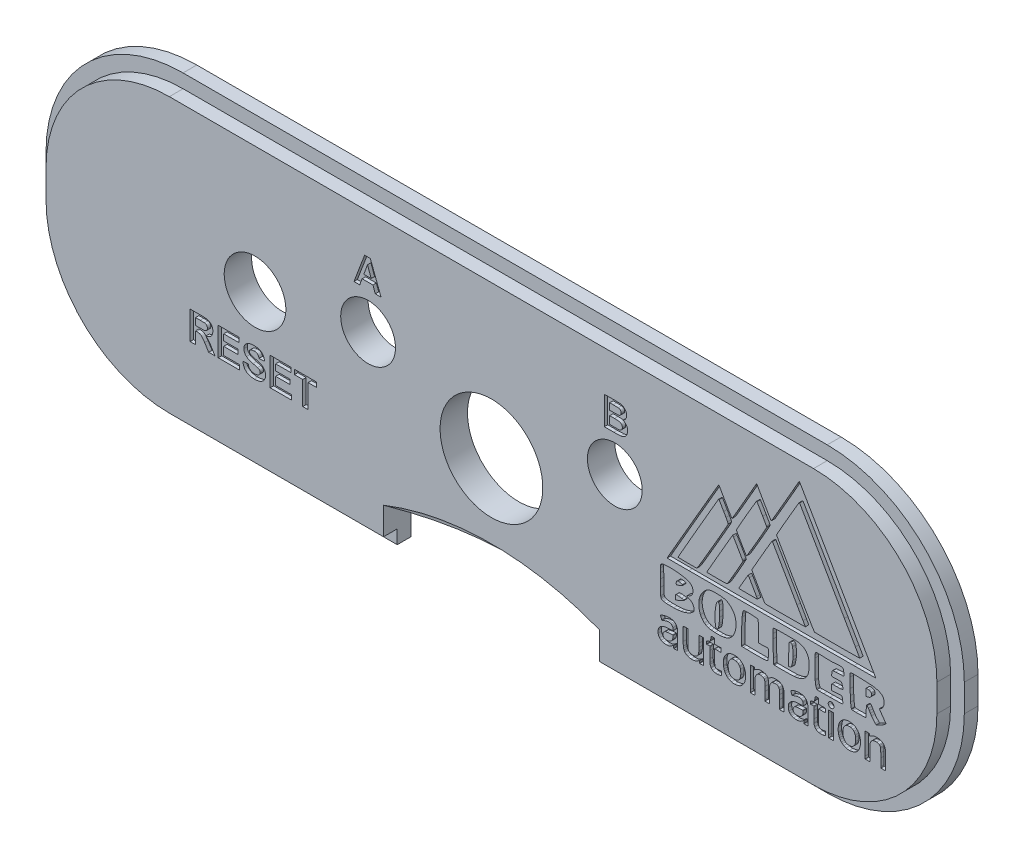
SolidWorks part; units mm, degrees
ref_plane "Front Plane" through (0, 0, 0) normal (0, 0, 1) x (1, 0, 0)
ref_plane "Top Plane" through (0, 0, 0) normal (0, 1, 0) x (1, 0, 0)
ref_plane "Right Plane" through (0, 0, 0) normal (1, 0, 0) x (0, 0, -1)
sketch "Sketch1" plane through (0, 0, 0) normal (0, 0, 1) x (1, 0, 0)
  line L1 (-33.5, -11) -> (33.5, -11)
  line L2 (-33.5, -11) -> (-33.5, 11)
  line L3 (-33.5, 11) -> (33.5, 11)
  line L4 (33.5, -11) -> (33.5, 11)
  line L5 (-33.5, -11) -> (33.5, 11) construction
  line L6 (-33.5, 11) -> (33.5, -11) construction
  point P0 (0, 0)
  dimension "D1" = 67
  dimension "D2" = 22
extrude "Boss-Extrude1" add sketch "Sketch1" along normal blind 1 contours L3 L4 L1 L2
fillet "Fillet1" radius 10 4 edges at (33.5, 11, 0.5) (33.5, -11, 0.5) (-33.5, -11, 0.5) (-33.5, 11, 0.5)
sketch "Sketch2" plane through (0, 0, 1) normal (0, 0, 1) x (1, 0, 0)
  line L8 (32.5, -1) -> (32.5, 1)
  line L9 (23.5, 10) -> (-23.5, 10)
  line L10 (-32.5, 1) -> (-32.5, -1)
  line L11 (-23.5, -10) -> (23.5, -10)
  line L12 (32.5, -1) -> (32.5, 1)
  line L13 (23.5, 10) -> (-23.5, 10)
  line L14 (-32.5, 1) -> (-32.5, -1)
  line L15 (-23.5, -10) -> (23.5, -10)
  arc A8 (32.5, 1) -> (23.5, 10) centre (23.5, 1) ccw
  arc A9 (-23.5, 10) -> (-32.5, 1) centre (-23.5, 1) ccw
  arc A10 (-32.5, -1) -> (-23.5, -10) centre (-23.5, -1) ccw
  arc A11 (23.5, -10) -> (32.5, -1) centre (23.5, -1) ccw
  arc A12 (32.5, 1) -> (23.5, 10) centre (23.5, 1) ccw
  arc A13 (-23.5, 10) -> (-32.5, 1) centre (-23.5, 1) ccw
  arc A14 (-32.5, -1) -> (-23.5, -10) centre (-23.5, -1) ccw
  arc A15 (23.5, -10) -> (32.5, -1) centre (23.5, -1) ccw
  dimension "D1" = 1
extrude "Boss-Extrude2" add sketch "Sketch2" along normal blind 1
sketch "Sketch3" plane through (0, 0, 0) normal (0, 0, -1) x (-1, 0, 0)
  line L0 (0, 0) -> (0, -11) construction
  line L1 (23.5, -11) -> (-23.5, -11) construction
  line L2 (-7.875, -14) -> (-7.875, -8)
  line L3 (-7.875, -14) -> (7.875, -14)
  line L4 (-7.875, -8) -> (7.875, -8)
  line L5 (7.875, -14) -> (7.875, -8)
  line L6 (-7.875, -14) -> (7.875, -8) construction
  line L7 (-7.875, -8) -> (7.875, -14) construction
  line L8 (23.5, -11) -> (-23.5, -11) construction
  dimension "D1" = 15.75
  dimension "D2" = 6
  dimension "D3" = 90
extrude "Cut-Extrude1" cut sketch "Sketch3" against normal through all
sketch "Sketch109" plane through (0, 0, 2) normal (0, 0, 1) x (1, 0, 0)
  line L0 (7.875, -8) -> (-7.875, -8) construction
  arc A0 (-7.875, -8) -> (7.875, -8) centre (0, -27.9219) cw
  point P3 (0, -6.5)
  dimension "D1" = 1.5
revolve "Cut-Revolve3" cut sketch "Sketch109" angle 360 about axis through (7.875, -8, 2) along (1, 0, 0) region at (0, -7.3982, 2)
sketch "Sketch112" plane through (0, 0, 0) normal (0, 0, -1) x (-1, 0, 0)
  line L0 (0, 0) -> (0, -11) construction
  line L1 (0, 0) -> (33.5, 0) construction
  line L2 (33.5, -1) -> (33.5, 1) construction
  line L3 (9, 0) -> (9, 2.38) construction
  line L4 (0, 0) -> (0, 11) construction
  line L5 (23.5, 11) -> (-23.5, 11) construction
  line L6 (0, 0) -> (-33.5, 0) construction
  line L7 (-33.5, -1) -> (-33.5, 1) construction
  line L9 (17.25, 0) -> (17.25, 0.8) construction
  circle A0 centre (0, -1.1) radius 3.75
  circle A1 centre (9, 2.38) radius 2
  circle A2 centre (-9, 2.38) radius 2
  circle A4 centre (17.25, 0.8) radius 2.25
  dimension "D2" = 7.5
  dimension "D5" = 4
  dimension "D11" = 4.5
  dimension "D1" = 1.1
  dimension "D3" = 2.38
  dimension "D4" = 9
  dimension "D9" = 0.8
  dimension "D10" = 17.25
extrude "Cut-Extrude2" cut sketch "Sketch112" against normal through all
sketch "Sketch113" plane through (0, 0, 2) normal (0, 0, 1) x (1, 0, 0)
  circle B0 centre (24.7803, -4.3035) radius 0.2103
  arc B1 (23.0498, 7.6782) -> (22.4641, 8.6806) centre (-50.9258, -34.8776) ccw
  arc B2 (22.4641, 8.6806) -> (22.314, 8.4273) centre (27.1246, 5.7481) ccw
  arc B3 (22.314, 8.4273) -> (21.9419, 7.7803) centre (222.0938, -106.9099) ccw
  arc B4 (20.9079, 5.9825) -> (21.9419, 7.7803) centre (-602.4956, 365.7341) ccw
  arc B5 (20.4342, 5.1705) -> (20.9079, 5.9825) centre (-80.1922, 64.4048) ccw
  arc B6 (20.4279, 5.1648) -> (20.4342, 5.1705) centre (20.4211, 5.1787) ccw
  arc B7 (20.4085, 5.162) -> (20.4279, 5.1648) centre (20.4139, 5.1931) ccw
  arc B8 (20.3929, 5.1705) -> (20.4085, 5.162) centre (20.4111, 5.1852) ccw
  arc B9 (20.1485, 5.5856) -> (20.3929, 5.1705) centre (46.8153, 21.0091) ccw
  arc B10 (19.8754, 6.0603) -> (20.1485, 5.5856) centre (97.988, 50.6909) ccw
  arc B11 (19.8754, 6.0603) -> (19.4298, 6.8395) centre (-513.4407, -298.3467) ccw
  arc B12 (19.4298, 6.8395) -> (19.3508, 6.9696) centre (18.1163, 6.1313) ccw
  arc B13 (19.3508, 6.9696) -> (19.2181, 6.7469) centre (22.9527, 4.672) ccw
  arc B14 (19.2181, 6.7469) -> (18.8904, 6.178) centre (165.0061, -77.6169) ccw
  arc B15 (17.9807, 4.5971) -> (18.8904, 6.178) centre (-631.1168, 379.1333) ccw
  arc B16 (17.5642, 3.8828) -> (17.9807, 4.5971) centre (-73.0363, 57.1929) ccw
  arc B17 (17.559, 3.8782) -> (17.5642, 3.8828) centre (17.5534, 3.8896) ccw
  arc B18 (17.5303, 3.8828) -> (17.559, 3.8782) centre (17.5479, 3.9004) ccw
  arc B19 (17.3436, 4.2026) -> (17.5303, 3.8828) centre (36.9073, 15.4072) ccw
  arc B20 (16.9792, 4.8473) -> (17.3436, 4.2026) centre (83.5983, 42.0848) ccw
  arc B21 (16.9792, 4.8473) -> (16.608, 5.488) centre (-8.8306, -9.6775) ccw
  arc B22 (16.608, 5.488) -> (16.6012, 5.494) centre (16.5938, 5.4789) ccw
  arc B23 (16.6012, 5.494) -> (16.5804, 5.4971) centre (16.5861, 5.4635) ccw
  arc B24 (16.5804, 5.4971) -> (16.5639, 5.488) centre (16.583, 5.4728) ccw
  arc B25 (16.5639, 5.488) -> (15.6903, 3.9876) centre (563.2563, -313.8159) ccw
  arc B26 (15.6903, 3.9876) -> (13.0854, -0.5227) centre (988.6695, -560.9533) ccw
  arc B27 (13.0854, -0.5227) -> (12.8193, -0.9943) centre (28.6752, -9.63) ccw
  arc B28 (12.8193, -0.9943) -> (14.4045, -0.9969) centre (13.8688, 157.752) ccw
  arc B29 (14.4045, -0.9969) -> (26.458, -0.9759) centre (11.1994, 5300.4417) ccw
  arc B30 (26.458, -0.9759) -> (28.0431, -0.9678) centre (26.4404, 157.9147) ccw
  arc B31 (28.0431, -0.9678) -> (27.4665, 0.0399) centre (-46.3137, -42.8404) ccw
  arc B32 (27.4665, 0.0399) -> (23.0498, 7.6782) centre (-2435.592, -1419.0663) ccw
  arc B33 (22.4588, 7.3225) -> (22.4427, 7.3136) centre (22.4614, 7.2987) ccw
  arc B34 (22.4427, 7.3136) -> (21.2219, 5.2134) centre (242.6481, -122.0921) ccw
  arc B35 (21.2219, 5.2134) -> (20.9228, 4.6838) centre (57.5521, -15.6522) ccw
  arc B36 (20.9228, 4.6838) -> (20.806, 4.4561) centre (22.5174, 3.7223) ccw
  arc B37 (20.806, 4.4561) -> (21.0886, 3.9431) centre (29.0248, 8.6476) ccw
  arc B38 (21.0886, 3.9431) -> (21.7639, 2.7668) centre (193.5014, 102.1518) ccw
  arc B39 (21.7639, 2.7668) -> (22.574, 1.3717) centre (359.7991, 198.1317) ccw
  arc B40 (22.574, 1.3717) -> (23.2609, 0.2021) centre (193.9122, 101.2111) ccw
  arc B41 (23.2609, 0.2021) -> (23.5665, -0.2976) centre (31.2761, 4.7607) ccw
  arc B42 (23.5665, -0.2976) -> (23.928, -0.3093) centre (23.8658, 3.3467) ccw
  arc B43 (23.928, -0.3093) -> (24.7484, -0.3128) centre (24.6753, 79.558) ccw
  arc B44 (24.7484, -0.3128) -> (26.5287, -0.3045) centre (24.7463, 191.7103) ccw
  arc B45 (26.5287, -0.3045) -> (26.8701, -0.2976) centre (26.5497, 7.0805) ccw
  arc B46 (26.8701, -0.2976) -> (26.5579, 0.2553) centre (5.1072, -12.2228) ccw
  arc B47 (26.5579, 0.2553) -> (25.7535, 1.6575) centre (-530.4511, -318.3624) ccw
  arc B48 (25.7535, 1.6575) -> (22.4855, 7.3136) centre (-1374.7342, -803.7385) ccw
  arc B49 (22.4855, 7.3136) -> (22.479, 7.3195) centre (22.4719, 7.3052) ccw
  arc B50 (22.479, 7.3195) -> (22.4588, 7.3225) centre (22.4644, 7.2902) ccw
  arc B51 (19.3455, 5.8495) -> (19.3295, 5.8408) centre (19.348, 5.8259) ccw
  arc B52 (19.3295, 5.8408) -> (18.7398, 4.8406) centre (147.9054, -70.6335) ccw
  arc B53 (18.7398, 4.8406) -> (17.878, 3.3272) centre (88.5187, -35.8996) ccw
  arc B54 (17.878, 3.3272) -> (17.8735, 3.3121) centre (17.9108, 3.3093) ccw
  arc B55 (17.8735, 3.3121) -> (17.8799, 3.2792) centre (17.9407, 3.3081) ccw
  arc B56 (17.8799, 3.2792) -> (17.8956, 3.2478) centre (18.1036, 3.3715) ccw
  arc B57 (17.8956, 3.2478) -> (18.1652, 2.768) centre (72.8714, 33.8162) ccw
  arc B58 (18.1652, 2.768) -> (18.5849, 2.0572) centre (39.8931, 15.1199) ccw
  arc B59 (18.5849, 2.0572) -> (18.5921, 2.0509) centre (18.6, 2.0671) ccw
  arc B60 (18.5921, 2.0509) -> (18.6139, 2.0477) centre (18.608, 2.0832) ccw
  arc B61 (18.6139, 2.0477) -> (18.6314, 2.0572) centre (18.6112, 2.0734) ccw
  arc B62 (18.6314, 2.0572) -> (18.9279, 2.5563) centre (-146.4854, 100.496) ccw
  arc B63 (18.9279, 2.5563) -> (19.5138, 3.5588) centre (-66.4571, 53.1324) ccw
  arc B64 (19.5138, 3.5588) -> (20.0829, 4.5708) centre (-30.3015, 32.237) ccw
  arc B65 (20.0829, 4.5708) -> (20.0842, 4.6057) centre (20.0467, 4.5897) ccw
  arc B66 (20.0842, 4.6057) -> (20.0764, 4.6241) centre (19.9691, 4.5677) ccw
  arc B67 (20.0764, 4.6241) -> (20.0564, 4.659) centre (19.5515, 4.3456) ccw
  arc B68 (20.0564, 4.659) -> (19.7882, 5.1349) centre (-49.054, -33.97) ccw
  arc B69 (19.7882, 5.1349) -> (19.3722, 5.8408) centre (-3.5376, -8.1372) ccw
  arc B70 (19.3722, 5.8408) -> (19.3656, 5.8466) centre (19.3583, 5.8317) ccw
  arc B71 (19.3656, 5.8466) -> (19.3455, 5.8495) centre (19.351, 5.8169) ccw
  arc B72 (16.5809, 4.597) -> (16.5652, 4.5884) centre (16.5834, 4.574) ccw
  arc B73 (16.5652, 4.5884) -> (15.8757, 3.4009) centre (385.0113, -210.1417) ccw
  arc B74 (15.8757, 3.4009) -> (13.8222, -0.1701) centre (651.1096, -364.262) ccw
  arc B75 (13.8222, -0.1701) -> (13.6131, -0.5445) centre (23.6461, -5.902) ccw
  arc B76 (13.6131, -0.5445) -> (13.7546, -0.5514) centre (13.7475, 0.7526) ccw
  arc B77 (13.7546, -0.5514) -> (14.4889, -0.5597) centre (14.4474, 28.3545) ccw
  arc B78 (14.4889, -0.5597) -> (14.8325, -0.5563) centre (14.5181, 13.5964) ccw
  arc B79 (14.8325, -0.5563) -> (14.994, -0.5445) centre (14.8532, 0.2758) ccw
  arc B80 (14.994, -0.5445) -> (15.2501, -0.1302) centre (9.6282, 3.0577) ccw
  arc B81 (15.2501, -0.1302) -> (15.8188, 0.8358) centre (-101.2446, 69.1044) ccw
  arc B82 (15.8188, 0.8358) -> (16.4879, 1.988) centre (-213.4808, 134.769) ccw
  arc B83 (16.4879, 1.988) -> (17.0452, 2.9609) centre (-100.4773, 69.6297) ccw
  arc B84 (17.0452, 2.9609) -> (17.2783, 3.389) centre (11.5032, 6.2562) ccw
  arc B85 (17.2783, 3.389) -> (17.2311, 3.4975) centre (16.8233, 3.2558) ccw
  arc B86 (17.2311, 3.4975) -> (17.1096, 3.7221) centre (10.5956, 0.0519) ccw
  arc B87 (17.1096, 3.7221) -> (16.9445, 4.0123) centre (-4.7311, -8.5085) ccw
  arc B88 (16.9445, 4.0123) -> (16.6069, 4.5884) centre (-26.7767, -21.22) ccw
  arc B89 (16.6069, 4.5884) -> (16.6005, 4.5941) centre (16.5936, 4.5799) ccw
  arc B90 (16.6005, 4.5941) -> (16.5809, 4.597) centre (16.5863, 4.5654) ccw
  arc B91 (20.4759, 3.8925) -> (20.4584, 3.8828) centre (20.4788, 3.8664) ccw
  arc B92 (20.4584, 3.8828) -> (19.871, 2.8814) centre (94.2003, -40.0406) ccw
  arc B93 (19.871, 2.8814) -> (19.0069, 1.3693) centre (174.5101, -86.4937) ccw
  arc B94 (19.0069, 1.3693) -> (19.0069, 1.3252) centre (19.0468, 1.3473) ccw
  arc B95 (19.2208, 0.95) -> (19.0069, 1.3252) centre (-322.3255, -193.495) ccw
  arc B96 (19.2208, 0.95) -> (19.6927, 0.1288) centre (112.6319, 54.0895) ccw
  arc B97 (19.6927, 0.1288) -> (19.8715, -0.1704) centre (32.0786, 7.3272) ccw
  arc B98 (19.8715, -0.1704) -> (19.9594, -0.2976) centre (20.5255, 0.1875) ccw
  arc B99 (19.9594, -0.2976) -> (20.2834, -0.3093) centre (20.2289, 2.6582) ccw
  arc B100 (20.2834, -0.3093) -> (21.0141, -0.3128) centre (20.9488, 62.9553) ccw
  arc B101 (21.0141, -0.3128) -> (22.5976, -0.3045) centre (21.011, 151.3463) ccw
  arc B102 (22.5976, -0.3045) -> (22.9013, -0.2976) centre (22.6157, 5.5588) ccw
  arc B103 (22.9013, -0.2976) -> (22.7323, 0.0083) centre (16.1932, -3.8033) ccw
  arc B104 (22.7323, 0.0083) -> (22.2939, 0.7793) centre (-142.6654, -93.5283) ccw
  arc B105 (22.2939, 0.7793) -> (20.5049, 3.8828) centre (-368.428, -222.3883) ccw
  arc B106 (20.5049, 3.8828) -> (20.4978, 3.8893) centre (20.4901, 3.8737) ccw
  arc B107 (20.4978, 3.8893) -> (20.4759, 3.8925) centre (20.482, 3.8575) ccw
  arc B108 (17.6618, 2.7554) -> (17.6055, 2.8413) centre (17.0631, 2.4241) ccw
  arc B109 (17.6055, 2.8413) -> (17.403, 2.5012) centre (26.1163, -2.4553) ccw
  arc B110 (17.403, 2.5012) -> (15.9054, -0.0933) centre (300.8898, -162.8679) ccw
  arc B111 (15.9054, -0.0933) -> (15.7121, -0.4387) centre (24.5344, -5.1476) ccw
  arc B112 (15.7121, -0.4387) -> (15.8635, -0.4456) centre (15.8557, 1.0428) ccw
  arc B113 (15.8635, -0.4456) -> (16.65, -0.4539) centre (16.6054, 32.7305) ccw
  arc B114 (16.65, -0.4539) -> (17.0173, -0.4504) centre (16.6812, 15.719) ccw
  arc B115 (17.0173, -0.4504) -> (17.1887, -0.4387) centre (17.0401, 0.4741) ccw
  arc B116 (17.1887, -0.4387) -> (17.2918, -0.2862) centre (16.3924, 0.2107) ccw
  arc B117 (17.2918, -0.2862) -> (17.5092, 0.0781) centre (1.0663, 9.6436) ccw
  arc B118 (17.5092, 0.0781) -> (18.3366, 1.5457) centre (-30.7808, 28.2709) ccw
  arc B119 (18.3366, 1.5457) -> (18.3415, 1.5643) centre (18.2995, 1.5655) ccw
  arc B120 (18.3415, 1.5643) -> (18.3312, 1.6044) centre (18.2613, 1.565) ccw
  arc B121 (18.3312, 1.6044) -> (18.3101, 1.6427) centre (17.9362, 1.4125) ccw
  arc B122 (18.3101, 1.6427) -> (17.6618, 2.7554) centre (-25.6685, -23.2378) ccw
  arc B123 (18.81, 0.7616) -> (18.7344, 0.8833) centre (17.6322, 0.1141) ccw
  arc B124 (18.7344, 0.8833) -> (18.6576, 0.7616) centre (19.84, 0.1009) ccw
  arc B125 (18.6576, 0.7616) -> (18.1168, -0.1705) centre (55.0739, -20.9883) ccw
  arc B126 (18.1168, -0.1705) -> (18.0493, -0.2976) centre (19.2775, -0.8691) ccw
  arc B127 (18.0493, -0.2976) -> (18.1925, -0.3029) centre (18.1707, 1.0404) ccw
  arc B128 (18.1925, -0.3029) -> (19.2654, -0.3029) centre (18.7287, 41.7799) ccw
  arc B129 (19.2654, -0.3029) -> (19.4087, -0.2976) centre (19.2872, 1.0437) ccw
  arc B130 (19.4087, -0.2976) -> (19.3422, -0.1705) centre (18.1829, -0.8575) ccw
  arc B131 (19.3422, -0.1705) -> (18.81, 0.7616) centre (-17.5144, -20.5975) ccw
  arc B132 (16.5486, -1.4301) -> (16.0876, -1.4353) centre (16.3743, -6.4364) ccw
  arc B133 (16.0876, -1.4353) -> (16.0367, -1.4411) centre (16.1112, -1.8709) ccw
  arc B134 (16.0367, -1.4411) -> (15.9369, -1.4676) centre (16.1406, -2.0333) ccw
  arc B135 (15.9369, -1.4676) -> (15.7472, -1.5503) centre (16.4093, -2.8091) ccw
  arc B136 (15.7472, -1.5503) -> (15.6202, -1.6381) centre (16.0494, -2.1232) ccw
  arc B137 (15.6202, -1.6381) -> (15.5576, -1.6996) centre (16.7343, -2.8354) ccw
  arc B138 (15.5576, -1.6996) -> (15.338, -1.9733) centre (16.9564, -3.0471) ccw
  arc B139 (15.338, -1.9733) -> (15.2803, -2.0748) centre (15.9772, -2.4033) ccw
  arc B140 (15.2803, -2.0748) -> (15.2145, -2.2379) centre (16.5861, -2.6968) ccw
  arc B141 (15.2145, -2.2379) -> (15.144, -2.5201) centre (16.6587, -2.7488) ccw
  arc B142 (15.144, -2.5201) -> (15.2498, -3.3491) centre (16.6176, -2.7532) ccw
  arc B143 (15.2498, -3.3491) -> (15.3866, -3.5876) centre (16.3259, -2.8904) ccw
  arc B144 (15.3866, -3.5876) -> (15.5144, -3.7195) centre (15.9962, -3.1249) ccw
  arc B145 (15.5144, -3.7195) -> (15.559, -3.7543) centre (17.4776, -1.2454) ccw
  arc B146 (15.559, -3.7543) -> (15.652, -3.8191) centre (16.3083, -2.7781) ccw
  arc B147 (15.652, -3.8191) -> (15.8191, -3.8916) centre (15.9822, -3.2867) ccw
  arc B148 (15.8191, -3.8916) -> (16.0265, -3.9321) centre (16.1609, -2.6946) ccw
  arc B149 (16.0265, -3.9321) -> (16.3078, -3.9544) centre (16.4156, -0.8066) ccw
  arc B150 (16.3078, -3.9544) -> (16.6859, -3.9563) centre (16.5253, 1.7828) ccw
  arc B151 (16.6859, -3.9563) -> (16.9255, -3.9312) centre (16.6295, -2.262) ccw
  arc B152 (16.9255, -3.9312) -> (17.2254, -3.843) centre (16.6243, -2.3532) ccw
  arc B153 (17.2254, -3.843) -> (17.4017, -3.7372) centre (16.9716, -3.2201) ccw
  arc B154 (17.4017, -3.7372) -> (17.5303, -3.6164) centre (16.4457, -2.5904) ccw
  arc B155 (17.5303, -3.6164) -> (17.6694, -3.4207) centre (16.8541, -2.9884) ccw
  arc B156 (17.6694, -3.4207) -> (17.7667, -3.1919) centre (16.4829, -2.7811) ccw
  arc B157 (17.7667, -3.1919) -> (17.8329, -2.8891) centre (16.1896, -2.6884) ccw
  arc B158 (17.8329, -2.8891) -> (17.8353, -2.5388) centre (16.3148, -2.7038) ccw
  arc B159 (17.8353, -2.5388) -> (17.7961, -2.2965) centre (16.2196, -2.6759) ccw
  arc B160 (17.7961, -2.2965) -> (17.7281, -2.1144) centre (16.7108, -2.598) ccw
  arc B161 (17.7281, -2.1144) -> (17.6222, -1.9292) centre (16.754, -2.5481) ccw
  arc B162 (17.6222, -1.9292) -> (17.4188, -1.7118) centre (16.6162, -2.6666) ccw
  arc B163 (17.4188, -1.7118) -> (17.3267, -1.6325) centre (16.2641, -2.9595) ccw
  arc B164 (17.3267, -1.6325) -> (17.2254, -1.5676) centre (16.9399, -2.1252) ccw
  arc B165 (17.2254, -1.5676) -> (17.0819, -1.5068) centre (16.6322, -2.7691) ccw
  arc B166 (17.0819, -1.5068) -> (16.8549, -1.4529) centre (16.7201, -2.5248) ccw
  arc B167 (16.8549, -1.4529) -> (16.5486, -1.4301) centre (16.4215, -5.2042) ccw
  arc B168 (13.5371, -1.5141) -> (13.3183, -1.497) centre (13.0762, -6.0045) ccw
  arc B169 (13.3183, -1.497) -> (13.0559, -1.4905) centre (12.9776, -9.9234) ccw
  arc B170 (13.0559, -1.4905) -> (12.688, -1.502) centre (13.0154, -6.0778) ccw
  arc B171 (12.688, -1.502) -> (12.5158, -1.5235) centre (12.8283, -3.33) ccw
  arc B172 (12.5158, -1.5235) -> (12.4299, -1.5633) centre (12.5529, -1.7159) ccw
  arc B173 (12.4299, -1.5633) -> (12.3394, -1.6734) centre (12.617, -1.8094) ccw
  arc B174 (12.3394, -1.6734) -> (12.3254, -1.7449) centre (12.5721, -1.756) ccw
  arc B175 (12.3254, -1.7449) -> (12.3194, -1.8664) centre (14.0508, -1.8919) ccw
  arc B176 (12.3194, -1.8664) -> (12.3202, -2.1741) centre (20.0405, -1.9994) ccw
  arc B177 (12.323, -2.5748) -> (12.3202, -2.1741) centre (-15.8258, -2.5727) ccw
  arc B178 (12.323, -2.5748) -> (12.3294, -3.0901) centre (48.6349, -2.3817) ccw
  arc B179 (12.3294, -3.0901) -> (12.3482, -3.6049) centre (28.8759, -2.7439) ccw
  arc B180 (12.3482, -3.6049) -> (12.3565, -3.6802) centre (12.9717, -3.5745) ccw
  arc B181 (12.3565, -3.6802) -> (12.3802, -3.7512) centre (12.614, -3.6335) ccw
  arc B182 (12.3802, -3.7512) -> (12.4284, -3.8044) centre (12.5076, -3.6841) ccw
  arc B183 (12.4284, -3.8044) -> (12.4962, -3.8328) centre (12.5505, -3.6086) ccw
  arc B184 (12.4962, -3.8328) -> (12.5687, -3.8518) centre (13.2941, -0.9357) ccw
  arc B185 (12.5687, -3.8518) -> (12.7715, -3.8871) centre (12.835, -2.9214) ccw
  arc B186 (12.7715, -3.8871) -> (12.9831, -3.8974) centre (13.2923, 4.6179) ccw
  arc B187 (12.9831, -3.8974) -> (13.3007, -3.8959) centre (13.123, 0.1163) ccw
  arc B188 (13.3007, -3.8959) -> (13.567, -3.8805) centre (12.529, 11.787) ccw
  arc B189 (13.567, -3.8805) -> (13.8317, -3.8508) centre (13.3319, -0.5931) ccw
  arc B190 (13.8317, -3.8508) -> (14.0853, -3.7917) centre (13.5443, -2.0442) ccw
  arc B191 (14.0853, -3.7917) -> (14.4435, -3.6536) centre (13.2529, -1.0986) ccw
  arc B192 (14.4435, -3.6536) -> (14.5768, -3.5722) centre (14.1527, -3.0279) ccw
  arc B193 (14.5768, -3.5722) -> (14.6982, -3.4659) centre (13.8578, -2.6287) ccw
  arc B194 (14.6982, -3.4659) -> (14.7454, -3.4126) centre (14.2687, -3.0381) ccw
  arc B195 (14.7454, -3.4126) -> (14.7735, -3.3667) centre (14.5861, -3.2831) ccw
  arc B196 (14.7735, -3.3667) -> (14.7842, -3.325) centre (14.613, -3.3034) ccw
  arc B197 (14.7842, -3.325) -> (14.7814, -3.2358) centre (14.4897, -3.2898) ccw
  arc B198 (14.7814, -3.2358) -> (14.7647, -3.1463) centre (13.1551, -3.4919) ccw
  arc B199 (14.7647, -3.1463) -> (14.6601, -2.9252) centre (14.2905, -3.2354) ccw
  arc B200 (14.6601, -2.9252) -> (14.5795, -2.8464) centre (14.3385, -3.1735) ccw
  arc B201 (14.5795, -2.8464) -> (14.5219, -2.8117) centre (14.2727, -3.2906) ccw
  arc B202 (14.5219, -2.8117) -> (14.4609, -2.7824) centre (14.0283, -3.7602) ccw
  arc B203 (14.4609, -2.7824) -> (14.3989, -2.755) centre (4.4041, -25.5071) ccw
  arc B204 (14.3377, -2.726) -> (14.3989, -2.755) centre (14.8709, -1.6802) ccw
  arc B205 (14.2797, -2.6919) -> (14.3377, -2.726) centre (14.5948, -2.2218) ccw
  arc B206 (14.2732, -2.6842) -> (14.2797, -2.6919) centre (14.2913, -2.6756) ccw
  arc B207 (14.27, -2.6617) -> (14.2732, -2.6842) centre (14.3073, -2.6679) ccw
  arc B208 (14.2797, -2.6432) -> (14.27, -2.6617) centre (14.2986, -2.6649) ccw
  arc B209 (14.3253, -2.617) -> (14.2797, -2.6432) centre (14.4813, -2.9415) ccw
  arc B210 (14.3739, -2.5958) -> (14.3253, -2.617) centre (14.6421, -3.2761) ccw
  arc B211 (14.4235, -2.5762) -> (14.3739, -2.5958) centre (69.7908, -143.1383) ccw
  arc B212 (14.4235, -2.5762) -> (14.4721, -2.5551) centre (14.1528, -1.8888) ccw
  arc B213 (14.4721, -2.5551) -> (14.5725, -2.4817) centre (14.3283, -2.2528) ccw
  arc B214 (14.5725, -2.4817) -> (14.6413, -2.3966) centre (14.0572, -1.995) ccw
  arc B215 (14.6413, -2.3966) -> (14.6647, -2.3602) centre (14.3588, -2.1888) ccw
  arc B216 (14.6647, -2.3602) -> (14.6854, -2.2996) centre (14.5077, -2.2729) ccw
  arc B217 (14.6854, -2.2996) -> (14.6947, -2.1795) centre (12.9737, -2.1064) ccw
  arc B218 (14.6947, -2.1795) -> (14.6854, -1.9997) centre (13.7136, -2.1402) ccw
  arc B219 (14.6854, -1.9997) -> (14.6777, -1.9692) centre (14.499, -2.0301) ccw
  arc B220 (14.6777, -1.9692) -> (14.6503, -1.9119) centre (14.4139, -2.0602) ccw
  arc B221 (14.6503, -1.9119) -> (14.6148, -1.8586) centre (13.995, -2.3101) ccw
  arc B222 (14.6148, -1.8586) -> (14.5178, -1.7616) centre (14.286, -2.0904) ccw
  arc B223 (14.5178, -1.7616) -> (14.4503, -1.717) centre (13.8398, -2.7128) ccw
  arc B224 (14.4503, -1.717) -> (14.3414, -1.6646) centre (14.1322, -2.2392) ccw
  arc B225 (14.3414, -1.6646) -> (13.9533, -1.5676) centre (13.5828, -3.8742) ccw
  arc B226 (13.9533, -1.5676) -> (13.5371, -1.5141) centre (12.9153, -8.0023) ccw
  arc B227 (18.6217, -1.4925) -> (18.4336, -1.5058) centre (18.702, -3.9603) ccw
  arc B228 (18.4336, -1.5058) -> (18.4056, -1.517) centre (18.4401, -1.563) ccw
  arc B229 (18.4056, -1.517) -> (18.3841, -1.5403) centre (18.4616, -1.5904) ccw
  arc B230 (18.3841, -1.5403) -> (18.3677, -1.5713) centre (18.5415, -1.6433) ccw
  arc B231 (18.3677, -1.5713) -> (18.3552, -1.6054) centre (18.7265, -1.7217) ccw
  arc B232 (18.3552, -1.6054) -> (18.3149, -1.7775) centre (19.4863, -1.9612) ccw
  arc B233 (18.3149, -1.7775) -> (18.2925, -1.9909) centre (20.4574, -2.1102) ccw
  arc B234 (18.2925, -1.9909) -> (18.2519, -3.7855) centre (36.6022, -3.3029) ccw
  arc B235 (18.2519, -3.7855) -> (18.2573, -3.8517) centre (18.5874, -3.7914) ccw
  arc B236 (18.2573, -3.8517) -> (18.3718, -3.8582) centre (18.368, -2.916) ccw
  arc B237 (18.3718, -3.8582) -> (18.6546, -3.8645) centre (18.9767, 16.9509) ccw
  arc B238 (18.6546, -3.8645) -> (19.7918, -3.8695) centre (19.4232, 42.266) ccw
  arc B239 (19.7918, -3.8695) -> (20.1005, -3.8254) centre (19.7736, -2.6396) ccw
  arc B240 (20.1005, -3.8254) -> (20.1594, -3.7972) centre (20.0548, -3.654) ccw
  arc B241 (20.1594, -3.7972) -> (20.1799, -3.7636) centre (20.1242, -3.7527) ccw
  arc B242 (20.1799, -3.7636) -> (20.1938, -3.6214) centre (17.4074, -3.4193) ccw
  arc B243 (20.1938, -3.6214) -> (20.2034, -3.3355) centre (16.4576, -3.3535) ccw
  arc B244 (20.2034, -3.3355) -> (20.1975, -3.0492) centre (12.6779, -3.3471) ccw
  arc B245 (20.1975, -3.0492) -> (20.1946, -3.0368) centre (20.1616, -3.0509) ccw
  arc B246 (20.1946, -3.0368) -> (20.1534, -3.0051) centre (20.146, -3.0575) ccw
  arc B247 (20.1534, -3.0051) -> (20.0282, -3.0049) centre (20.087, -4.8247) ccw
  arc B248 (20.0282, -3.0049) -> (19.9029, -3.011) centre (20.1513, -6.8136) ccw
  arc B249 (19.7776, -3.019) -> (19.9029, -3.011) centre (16.9214, 42.6455) ccw
  arc B250 (19.6524, -3.0244) -> (19.7776, -3.019) centre (19.574, 0.2354) ccw
  arc B251 (19.5272, -3.0228) -> (19.6524, -3.0244) centre (19.6119, -1.341) ccw
  arc B252 (19.506, -3.0098) -> (19.5272, -3.0228) centre (19.5294, -2.9954) ccw
  arc B253 (19.4919, -2.9699) -> (19.506, -3.0098) centre (19.5643, -2.9669) ccw
  arc B254 (19.4831, -2.6894) -> (19.4919, -2.9699) centre (28.5511, -2.5447) ccw
  arc B255 (19.4804, -2.4087) -> (19.4831, -2.6894) centre (42.1277, -2.3279) ccw
  arc B256 (19.4804, -2.4087) -> (19.4785, -2.128) centre (-26.4071, -2.5726) ccw
  arc B257 (19.4785, -2.128) -> (19.4724, -1.8476) centre (8.101, -2.2382) ccw
  arc B258 (19.4724, -1.8476) -> (19.4567, -1.5676) centre (12.9871, -2.0704) ccw
  arc B259 (19.4567, -1.5676) -> (19.4504, -1.5516) centre (19.4268, -1.5701) ccw
  arc B260 (19.4504, -1.5516) -> (19.4364, -1.5395) centre (19.4117, -1.5824) ccw
  arc B261 (19.4364, -1.5395) -> (19.4176, -1.5311) centre (19.3882, -1.6217) ccw
  arc B262 (19.4176, -1.5311) -> (19.3773, -1.5235) centre (19.3684, -1.6811) ccw
  arc B263 (19.1886, -1.511) -> (19.3773, -1.5235) centre (20.9022, 23.0329) ccw
  arc B264 (19.1886, -1.511) -> (18.9995, -1.4991) centre (18.1817, -15.9343) ccw
  arc B265 (18.9995, -1.4991) -> (18.8104, -1.4916) centre (18.6845, -7.0578) ccw
  arc B266 (18.8104, -1.4916) -> (18.6217, -1.4925) centre (18.7329, -4.9126) ccw
  arc B267 (25.1452, -1.5058) -> (25.241, -1.5021) centre (25.029, 2.7137) ccw
  arc B268 (25.3374, -1.4981) -> (25.241, -1.5021) centre (25.5182, -7.0188) ccw
  arc B269 (25.4335, -1.4977) -> (25.3374, -1.4981) centre (25.3918, -3.1532) ccw
  arc B270 (25.5284, -1.5049) -> (25.4335, -1.4977) centre (25.4097, -2.4467) ccw
  arc B271 (25.6215, -1.5235) -> (25.5284, -1.5049) centre (25.4452, -2.1641) ccw
  arc B272 (25.6446, -1.5378) -> (25.6215, -1.5235) centre (25.6084, -1.5705) ccw
  arc B273 (25.6595, -1.5622) -> (25.6446, -1.5378) centre (25.5826, -1.5924) ccw
  arc B274 (25.6691, -1.5928) -> (25.6595, -1.5622) centre (25.4694, -1.6385) ccw
  arc B275 (25.676, -1.6253) -> (25.6691, -1.5928) centre (24.7347, -1.8098) ccw
  arc B276 (25.676, -1.6253) -> (25.6832, -1.6558) centre (26.0587, -1.5513) ccw
  arc B277 (25.7273, -1.8851) -> (25.6832, -1.6558) centre (24.492, -2.0037) ccw
  arc B278 (25.7296, -1.9761) -> (25.7273, -1.8851) centre (25.2539, -1.9424) ccw
  arc B279 (25.7256, -2.0011) -> (25.7296, -1.9761) centre (25.5859, -1.9663) ccw
  arc B280 (25.7179, -2.0169) -> (25.7256, -2.0011) centre (25.6911, -1.994) ccw
  arc B281 (25.655, -2.0252) -> (25.7179, -2.0169) centre (25.6581, -1.8064) ccw
  arc B282 (25.5097, -2.0319) -> (25.655, -2.0252) centre (25.3194, 3.716) ccw
  arc B283 (25.5097, -2.0319) -> (25.1135, -2.048) centre (26.0009, -18.9285) ccw
  arc B284 (25.1135, -2.048) -> (24.9335, -2.0615) centre (25.3154, -5.963) ccw
  arc B285 (24.9335, -2.0615) -> (24.8832, -2.0793) centre (24.9418, -2.1647) ccw
  arc B286 (24.8832, -2.0793) -> (24.863, -2.1056) centre (24.9079, -2.1192) ccw
  arc B287 (24.863, -2.1056) -> (24.8303, -2.3001) centre (25.8218, -2.3666) ccw
  arc B288 (24.8303, -2.3001) -> (24.8277, -2.4319) centre (26.277, -2.3946) ccw
  arc B289 (24.8277, -2.4319) -> (24.838, -2.4522) centre (24.8595, -2.4285) ccw
  arc B290 (24.838, -2.4522) -> (24.8718, -2.4672) centre (24.8752, -2.4138) ccw
  arc B291 (24.8718, -2.4672) -> (25.0834, -2.4655) centre (24.9571, 0.2169) ccw
  arc B292 (25.2952, -2.4573) -> (25.0834, -2.4655) centre (25.4192, -8.3929) ccw
  arc B293 (25.401, -2.4583) -> (25.2952, -2.4573) centre (25.3301, -4.3431) ccw
  arc B294 (25.4834, -2.4708) -> (25.401, -2.4583) centre (25.3966, -2.7666) ccw
  arc B295 (25.5333, -2.4936) -> (25.4834, -2.4708) centre (25.4345, -2.6434) ccw
  arc B296 (25.5611, -2.5235) -> (25.5333, -2.4936) centre (25.4743, -2.5765) ccw
  arc B297 (25.5862, -2.5818) -> (25.5611, -2.5235) centre (25.273, -2.6819) ccw
  arc B298 (25.6461, -2.7961) -> (25.5862, -2.5818) centre (22.7378, -3.4933) ccw
  arc B299 (25.6579, -2.8513) -> (25.6461, -2.7961) centre (24.6406, -3.041) ccw
  arc B300 (25.66, -2.8769) -> (25.6579, -2.8513) centre (25.5931, -2.8694) ccw
  arc B301 (25.6421, -2.8856) -> (25.66, -2.8769) centre (25.6316, -2.8414) ccw
  arc B302 (25.4949, -2.9194) -> (25.6421, -2.8856) centre (25.3134, -1.7924) ccw
  arc B303 (25.4451, -2.9258) -> (25.4949, -2.9194) centre (25.3861, -2.2617) ccw
  arc B304 (25.2052, -2.9334) -> (25.4451, -2.9258) centre (25.2161, 0.4849) ccw
  arc B305 (25.2052, -2.9334) -> (24.965, -2.9357) centre (25.1363, -8.3472) ccw
  arc B306 (24.965, -2.9357) -> (24.8454, -2.9434) centre (25.0325, -4.917) ccw
  arc B307 (24.8454, -2.9434) -> (24.8254, -2.9543) centre (24.851, -2.9773) ccw
  arc B308 (24.8254, -2.9543) -> (24.8101, -2.9875) centre (24.8687, -2.9945) ccw
  arc B309 (24.8101, -2.9875) -> (24.7963, -3.2595) centre (28.2105, -3.2957) ccw
  arc B310 (24.7963, -3.2595) -> (24.797, -3.3283) centre (26.2269, -3.28) ccw
  arc B311 (24.797, -3.3283) -> (24.8008, -3.3586) centre (24.8851, -3.3326) ccw
  arc B312 (24.8008, -3.3586) -> (24.8817, -3.3576) centre (24.8347, -2.8272) ccw
  arc B313 (25.2893, -3.3361) -> (24.8817, -3.3576) centre (53.4413, -542.2088) ccw
  arc B314 (25.478, -3.3283) -> (25.2893, -3.3361) centre (25.7113, -11.2794) ccw
  arc B315 (25.5647, -3.331) -> (25.478, -3.3283) centre (25.5105, -3.6886) ccw
  arc B316 (25.5783, -3.3595) -> (25.5647, -3.331) centre (25.5111, -3.374) ccw
  arc B317 (25.5927, -3.4169) -> (25.5783, -3.3595) centre (24.9418, -3.5504) ccw
  arc B318 (25.6303, -3.6401) -> (25.5927, -3.4169) centre (21.6718, -4.1912) ccw
  arc B319 (25.6303, -3.7989) -> (25.6303, -3.6401) centre (25.0726, -3.7195) ccw
  arc B320 (25.6112, -3.8237) -> (25.6303, -3.7989) centre (25.5977, -3.7935) ccw
  arc B321 (25.6038, -3.8254) -> (25.6112, -3.8237) centre (25.6031, -3.8054) ccw
  arc B322 (24.6981, -3.845) -> (25.6038, -3.8254) centre (21.7929, 151.1959) ccw
  arc B323 (24.2453, -3.8517) -> (24.6981, -3.845) centre (23.6475, 51.7796) ccw
  arc B324 (23.9033, -3.8521) -> (24.2453, -3.8517) centre (24.0561, 11.1473) ccw
  arc B325 (23.7556, -3.843) -> (23.9033, -3.8521) centre (23.8737, -3.1254) ccw
  arc B326 (23.7331, -3.8187) -> (23.7556, -3.843) centre (23.806, -3.7739) ccw
  arc B327 (23.7118, -3.7794) -> (23.7331, -3.8187) centre (23.9667, -3.6671) ccw
  arc B328 (23.6635, -3.6313) -> (23.7118, -3.7794) centre (24.5778, -3.415) ccw
  arc B329 (23.6228, -3.3426) -> (23.6635, -3.6313) centre (25.4283, -3.2349) ccw
  arc B330 (23.6194, -3.2697) -> (23.6228, -3.3426) centre (26.0104, -3.1971) ccw
  arc B331 (23.6106, -1.9115) -> (23.6194, -3.2697) centre (54.2194, -2.3919) ccw
  arc B332 (23.6157, -1.7461) -> (23.6106, -1.9115) centre (27.7007, -1.9542) ccw
  arc B333 (23.6218, -1.6636) -> (23.6157, -1.7461) centre (25.3639, -1.8342) ccw
  arc B334 (23.6316, -1.5972) -> (23.6218, -1.6636) centre (24.236, -1.7199) ccw
  arc B335 (23.6459, -1.5588) -> (23.6316, -1.5972) centre (23.7294, -1.6118) ccw
  arc B336 (23.6673, -1.5412) -> (23.6459, -1.5588) centre (23.7065, -1.6108) ccw
  arc B337 (23.7287, -1.5207) -> (23.6673, -1.5412) centre (23.763, -1.7256) ccw
  arc B338 (23.7958, -1.5147) -> (23.7287, -1.5207) centre (23.8012, -1.9511) ccw
  arc B339 (24.0146, -1.5157) -> (23.7958, -1.5147) centre (23.8765, -7.8182) ccw
  arc B340 (24.2333, -1.5224) -> (24.0146, -1.5157) centre (23.7499, -13.5996) ccw
  arc B341 (24.452, -1.5313) -> (24.2333, -1.5224) centre (18.5009, -144.7603) ccw
  arc B342 (24.452, -1.5313) -> (24.6707, -1.5388) centre (25.0559, 13.0025) ccw
  arc B343 (24.6707, -1.5388) -> (24.8894, -1.5411) centre (24.8538, 5.3738) ccw
  arc B344 (24.8894, -1.5411) -> (24.9919, -1.5291) centre (24.8665, -0.9056) ccw
  arc B345 (25.0938, -1.5103) -> (24.9919, -1.5291) centre (25.3101, -2.9685) ccw
  arc B346 (25.1452, -1.5058) -> (25.0938, -1.5103) centre (25.1584, -1.9605) ccw
  arc B347 (22.6059, -1.5824) -> (22.2701, -1.5147) centre (22.2407, -2.5274) ccw
  arc B348 (22.2701, -1.5147) -> (21.9402, -1.5104) centre (20.7588, -106.8427) ccw
  arc B349 (21.9402, -1.5104) -> (21.2803, -1.5084) centre (21.4869, -40.7699) ccw
  arc B350 (21.2803, -1.5084) -> (20.6208, -1.5235) centre (21.4133, -21.7125) ccw
  arc B351 (20.6208, -1.5235) -> (20.6034, -1.5276) centre (20.6235, -1.5744) ccw
  arc B352 (20.6034, -1.5276) -> (20.5591, -1.5852) centre (20.6326, -1.5958) ccw
  arc B353 (20.5591, -1.5852) -> (20.5513, -1.8972) centre (31.4305, -2.0147) ccw
  arc B354 (20.5513, -1.8972) -> (20.5497, -2.241) centre (43.4432, -2.1698) ccw
  arc B355 (20.5497, -2.241) -> (20.5708, -3.4409) centre (62.0227, -2.113) ccw
  arc B356 (20.5708, -3.4409) -> (20.5944, -3.8077) centre (27.4894, -3.1805) ccw
  arc B357 (20.5944, -3.8077) -> (20.5986, -3.821) centre (20.6306, -3.8036) ccw
  arc B358 (20.5986, -3.821) -> (20.6473, -3.8518) centre (20.6509, -3.7922) ccw
  arc B359 (20.6473, -3.8518) -> (22.076, -3.843) centre (21.2164, 19.6928) ccw
  arc B360 (22.076, -3.843) -> (22.1457, -3.8375) centre (22.0377, -2.9119) ccw
  arc B361 (22.1457, -3.8375) -> (22.2836, -3.8139) centre (21.9882, -2.5042) ccw
  arc B362 (22.2836, -3.8139) -> (22.4653, -3.769) centre (21.5163, -0.3143) ccw
  arc B363 (22.4653, -3.769) -> (22.8345, -3.5784) centre (22.1669, -2.7382) ccw
  arc B364 (22.8345, -3.5784) -> (22.9492, -3.4638) centre (22.4483, -3.0776) ccw
  arc B365 (22.9492, -3.4638) -> (23.0638, -3.2785) centre (22.0866, -2.8017) ccw
  arc B366 (23.0638, -3.2785) -> (23.147, -3.004) centre (22.1412, -2.8493) ccw
  arc B367 (23.147, -3.004) -> (23.1738, -2.3713) centre (20.8886, -2.5911) ccw
  arc B368 (23.1738, -2.3713) -> (23.1344, -2.1673) centre (22.0206, -2.4886) ccw
  arc B369 (23.1344, -2.1673) -> (23.0197, -1.9115) centre (22.0155, -2.5153) ccw
  arc B370 (23.0197, -1.9115) -> (22.9722, -1.8439) centre (22.5346, -2.2019) ccw
  arc B371 (22.9722, -1.8439) -> (22.8874, -1.7528) centre (22.2499, -2.4308) ccw
  arc B372 (22.8874, -1.7528) -> (22.7463, -1.647) centre (22.4055, -2.2484) ccw
  arc B373 (22.7463, -1.647) -> (22.6059, -1.5824) centre (22.1431, -2.7731) ccw
  arc B374 (27.4738, -1.5601) -> (26.3799, -1.5235) centre (25.9874, -29.6272) ccw
  arc B375 (26.3799, -1.5235) -> (26.3226, -1.5279) centre (26.3752, -1.8358) ccw
  arc B376 (26.3226, -1.5279) -> (26.2233, -1.5553) centre (26.4052, -2.0209) ccw
  arc B377 (26.2233, -1.5553) -> (26.1925, -1.57) centre (26.2718, -1.6969) ccw
  arc B378 (26.1925, -1.57) -> (26.1771, -1.594) centre (26.2112, -1.5989) ccw
  arc B379 (26.1771, -1.594) -> (26.1681, -1.8373) centre (36.6785, -2.1054) ccw
  arc B380 (26.1681, -1.8373) -> (26.1696, -2.5678) centre (39.6767, -2.1749) ccw
  arc B381 (26.1696, -2.5678) -> (26.1839, -3.0077) centre (63.1085, -1.5861) ccw
  arc B382 (26.1839, -3.0077) -> (26.2049, -3.4009) centre (35.7768, -2.6925) ccw
  arc B383 (26.2049, -3.4009) -> (26.2565, -3.7901) centre (29.9239, -3.1059) ccw
  arc B384 (26.2565, -3.7901) -> (26.2683, -3.8137) centre (26.3057, -3.7802) ccw
  arc B385 (26.2683, -3.8137) -> (26.2905, -3.8309) centre (26.3276, -3.76) ccw
  arc B386 (26.2905, -3.8309) -> (26.3191, -3.8424) centre (26.3593, -3.7014) ccw
  arc B387 (26.3191, -3.8424) -> (26.3799, -3.8518) centre (26.3862, -3.6091) ccw
  arc B388 (26.3799, -3.8518) -> (26.5975, -3.8542) centre (26.557, 2.276) ccw
  arc B389 (26.5975, -3.8542) -> (27.2502, -3.8338) centre (26.5385, 8.474) ccw
  arc B390 (27.2502, -3.8338) -> (27.3232, -3.825) centre (27.2462, -3.4947) ccw
  arc B391 (27.3232, -3.825) -> (27.331, -3.7376) centre (26.8592, -3.7395) ccw
  arc B392 (27.331, -3.7376) -> (27.3384, -3.5402) centre (14.7555, -3.1676) ccw
  arc B393 (27.3526, -3.1093) -> (27.3384, -3.5402) centre (98.923, -5.6803) ccw
  arc B394 (27.3597, -3.0228) -> (27.3526, -3.1093) centre (27.8643, -3.1077) ccw
  arc B395 (27.369, -3.017) -> (27.3597, -3.0228) centre (27.3804, -3.0456) ccw
  arc B396 (27.3942, -3.0131) -> (27.369, -3.017) centre (27.3896, -3.067) ccw
  arc B397 (27.4149, -3.0228) -> (27.3942, -3.0131) centre (27.3925, -3.0438) ccw
  arc B398 (27.497, -3.1422) -> (27.4149, -3.0228) centre (25.5379, -4.3999) ccw
  arc B399 (27.5735, -3.2655) -> (27.497, -3.1422) centre (23.4076, -5.7675) ccw
  arc B400 (27.5735, -3.2655) -> (27.6484, -3.3899) centre (79.8937, 28.1583) ccw
  arc B401 (27.6484, -3.3899) -> (27.7255, -3.5127) centre (31.2319, -1.2261) ccw
  arc B402 (27.7255, -3.5127) -> (27.991, -3.8351) centre (29.2677, -2.5135) ccw
  arc B403 (27.991, -3.8351) -> (28.0458, -3.8835) centre (28.4992, -3.3151) ccw
  arc B404 (28.0458, -3.8835) -> (28.0821, -3.9047) centre (28.1154, -3.806) ccw
  arc B405 (28.0821, -3.9047) -> (28.1273, -3.8946) centre (28.0799, -3.7892) ccw
  arc B406 (28.1273, -3.8946) -> (28.2051, -3.8616) centre (27.7835, -2.975) ccw
  arc B407 (28.2051, -3.8616) -> (28.4001, -3.7612) centre (26.9134, -1.1149) ccw
  arc B408 (28.4001, -3.7612) -> (28.5602, -3.6636) centre (27.4328, -1.9943) ccw
  arc B409 (28.5602, -3.6636) -> (28.7658, -3.5053) centre (27.116, -1.5741) ccw
  arc B410 (28.7658, -3.5053) -> (28.7876, -3.4814) centre (28.7127, -3.4349) ccw
  arc B411 (28.7876, -3.4814) -> (28.7573, -3.4319) centre (28.5735, -3.5788) ccw
  arc B412 (28.7573, -3.4319) -> (28.6777, -3.3203) centre (22.8185, -7.5809) ccw
  arc B413 (28.4592, -3.0148) -> (28.6777, -3.3203) centre (50.41, 12.4519) ccw
  arc B414 (28.3643, -2.8729) -> (28.4592, -3.0148) centre (31.7955, -0.6812) ccw
  arc B415 (28.3382, -2.8234) -> (28.3643, -2.8729) centre (28.67, -2.6799) ccw
  arc B416 (28.3244, -2.7724) -> (28.3382, -2.8234) centre (28.4993, -2.7525) ccw
  arc B417 (28.3271, -2.752) -> (28.3244, -2.7724) centre (28.3737, -2.7685) ccw
  arc B418 (28.341, -2.7361) -> (28.3271, -2.752) centre (28.3611, -2.7677) ccw
  arc B419 (28.3656, -2.7226) -> (28.341, -2.7361) centre (28.4256, -2.8609) ccw
  arc B420 (28.3958, -2.7097) -> (28.3656, -2.7226) centre (28.8204, -3.7452) ccw
  arc B421 (28.3958, -2.7097) -> (28.4264, -2.6957) centre (28.2339, -2.3149) ccw
  arc B422 (28.4264, -2.6957) -> (28.4525, -2.6788) centre (28.3651, -2.5724) ccw
  arc B423 (28.4525, -2.6788) -> (28.5045, -2.6309) centre (27.8851, -2.0111) ccw
  arc B424 (28.5045, -2.6309) -> (28.5672, -2.5465) centre (28.2416, -2.3702) ccw
  arc B425 (28.5672, -2.5465) -> (28.5904, -2.4978) centre (27.3897, -1.9555) ccw
  arc B426 (28.5904, -2.4978) -> (28.6284, -2.3963) centre (27.8608, -2.1667) ccw
  arc B427 (28.6284, -2.3963) -> (28.6465, -2.2908) centre (28.1753, -2.2641) ccw
  arc B428 (28.6465, -2.2908) -> (28.6427, -2.1506) centre (27.6759, -2.2471) ccw
  arc B429 (28.6427, -2.1506) -> (28.5936, -1.9468) centre (27.8749, -2.2277) ccw
  arc B430 (28.5936, -1.9468) -> (28.5721, -1.9044) centre (28.3237, -2.0573) ccw
  arc B431 (28.5721, -1.9044) -> (28.4741, -1.798) centre (28.245, -2.1072) ccw
  arc B432 (28.4741, -1.798) -> (28.3737, -1.7355) centre (28.1102, -2.2706) ccw
  arc B433 (28.3737, -1.7355) -> (28.2437, -1.6803) centre (27.9115, -2.6437) ccw
  arc B434 (28.2437, -1.6803) -> (28.1085, -1.6381) centre (27.5842, -3.5557) ccw
  arc B435 (28.1085, -1.6381) -> (27.7469, -1.5764) centre (27.636, -3.316) ccw
  arc B436 (27.7469, -1.5764) -> (27.4738, -1.5601) centre (26.3357, -22.8943) ccw
  arc B437 (21.9173, -1.8939) -> (21.8203, -1.841) centre (21.808, -1.9789) ccw
  arc B438 (21.8203, -1.841) -> (21.7485, -1.8538) centre (21.813, -2.0075) ccw
  arc B439 (21.7485, -1.8538) -> (21.7311, -1.8667) centre (21.7719, -1.9034) ccw
  arc B440 (21.7311, -1.8667) -> (21.7233, -1.8851) centre (21.7551, -1.8878) ccw
  arc B441 (21.7233, -1.8851) -> (21.7022, -2.2358) centre (30.4391, -2.5838) ccw
  arc B442 (21.7022, -2.2358) -> (21.6837, -3.2904) centre (43.9044, -3.1535) ccw
  arc B443 (21.6837, -3.2904) -> (21.6878, -3.4032) centre (22.623, -3.313) ccw
  arc B444 (21.6878, -3.4032) -> (21.7027, -3.4066) centre (21.7019, -3.376) ccw
  arc B445 (21.7027, -3.4066) -> (21.7682, -3.4029) centre (21.7189, -3.1096) ccw
  arc B446 (21.7682, -3.4029) -> (21.8379, -3.3844) centre (21.7308, -3.1223) ccw
  arc B447 (21.8379, -3.3844) -> (21.866, -3.3591) centre (21.8065, -3.3214) ccw
  arc B448 (21.866, -3.3591) -> (21.8908, -3.305) centre (21.7134, -3.2562) ccw
  arc B449 (21.8908, -3.305) -> (21.9508, -3.08) centre (20.2671, -2.7519) ccw
  arc B450 (21.9508, -3.08) -> (21.9861, -2.8682) centre (18.3301, -2.3681) ccw
  arc B451 (21.9861, -2.8682) -> (22.0055, -2.6347) centre (20.0368, -2.5885) ccw
  arc B452 (22.0055, -2.6347) -> (21.9702, -2.035) centre (17.5101, -2.5983) ccw
  arc B453 (21.9702, -2.035) -> (21.9654, -2.005) centre (21.6078, -2.078) ccw
  arc B454 (21.9654, -2.005) -> (21.9173, -1.8939) centre (21.6818, -2.0618) ccw
  arc B455 (16.5416, -1.9063) -> (16.511, -1.9027) centre (16.5203, -1.9556) ccw
  arc B456 (16.511, -1.9027) -> (16.4931, -1.9144) centre (16.5286, -1.9492) ccw
  arc B457 (16.4931, -1.9144) -> (16.4704, -1.939) centre (16.6415, -2.0746) ccw
  arc B458 (16.4704, -1.939) -> (16.4266, -2.0083) centre (16.7474, -2.162) ccw
  arc B459 (16.4266, -2.0083) -> (16.414, -2.0438) centre (16.5889, -2.0863) ccw
  arc B460 (16.414, -2.0438) -> (16.3186, -2.6494) centre (20.9477, -3.0682) ccw
  arc B461 (16.3186, -2.6494) -> (16.3053, -2.9365) centre (19.6571, -2.9476) ccw
  arc B462 (16.3053, -2.9365) -> (16.3177, -3.2049) centre (19.7758, -2.9109) ccw
  arc B463 (16.3177, -3.2049) -> (16.3434, -3.4726) centre (25.2633, -2.4807) ccw
  arc B464 (16.3434, -3.4726) -> (16.3648, -3.5773) centre (16.869, -3.42) ccw
  arc B465 (16.3648, -3.5773) -> (16.3963, -3.6401) centre (16.6054, -3.4957) ccw
  arc B466 (16.3963, -3.6401) -> (16.4082, -3.6515) centre (16.4334, -3.6131) ccw
  arc B467 (16.4082, -3.6515) -> (16.4757, -3.6578) centre (16.448, -3.5902) ccw
  arc B468 (16.4757, -3.6578) -> (16.507, -3.6329) centre (16.4424, -3.5838) ccw
  arc B469 (16.507, -3.6329) -> (16.5374, -3.5784) centre (16.3576, -3.5137) ccw
  arc B470 (16.5374, -3.5784) -> (16.5904, -3.3844) centre (15.8302, -3.2813) ccw
  arc B471 (16.5904, -3.3844) -> (16.6076, -3.2437) centre (2.4774, -1.5797) ccw
  arc B472 (16.6076, -3.2437) -> (16.6461, -2.8203) centre (8.913, -2.3311) ccw
  arc B473 (16.6461, -2.8203) -> (16.6507, -2.4351) centre (12.507, -2.5786) ccw
  arc B474 (16.6507, -2.4351) -> (16.6256, -2.0703) centre (10.9378, -2.644) ccw
  arc B475 (16.6256, -2.0703) -> (16.5815, -1.938) centre (16.3216, -2.0981) ccw
  arc B476 (16.5815, -1.938) -> (16.5416, -1.9063) centre (16.508, -1.9896) ccw
  arc B477 (27.3613, -1.958) -> (27.3331, -1.9645) centre (27.3637, -2.0334) ccw
  arc B478 (27.3331, -1.9645) -> (27.3268, -2.0042) centre (27.4546, -2.0039) ccw
  arc B479 (27.3268, -2.0042) -> (27.3218, -2.0956) centre (29.6911, -2.1805) ccw
  arc B480 (27.3218, -2.0956) -> (27.3148, -2.4583) centre (36.9596, -2.4628) ccw
  arc B481 (27.3148, -2.4583) -> (27.3324, -2.476) centre (27.3331, -2.4577) ccw
  arc B482 (27.3324, -2.476) -> (27.3829, -2.4676) centre (22.7658, 25.2909) ccw
  arc B483 (27.3829, -2.4676) -> (27.4833, -2.4474) centre (27.1523, -1.0629) ccw
  arc B484 (27.4833, -2.4474) -> (27.5794, -2.4142) centre (27.3462, -1.8946) ccw
  arc B485 (27.5794, -2.4142) -> (27.6097, -2.397) centre (27.4842, -2.2112) ccw
  arc B486 (27.6097, -2.397) -> (27.6635, -2.3516) centre (27.4191, -2.1169) ccw
  arc B487 (27.6635, -2.3516) -> (27.7117, -2.2996) centre (26.8627, -1.5612) ccw
  arc B488 (27.7117, -2.2996) -> (27.7381, -2.2379) centre (27.6341, -2.2298) ccw
  arc B489 (27.7381, -2.2379) -> (27.7291, -2.1239) centre (27.2908, -2.2161) ccw
  arc B490 (27.7291, -2.1239) -> (27.6985, -2.057) centre (27.5392, -2.1703) ccw
  arc B491 (27.6985, -2.057) -> (27.5816, -1.9756) centre (27.5204, -2.188) ccw
  arc B492 (27.5816, -1.9756) -> (27.5007, -1.9591) centre (27.4508, -2.4117) ccw
  arc B493 (27.5007, -1.9591) -> (27.3613, -1.958) centre (27.4257, -2.6041) ccw
  arc B494 (13.8973, -2.1102) -> (13.7329, -2.0615) centre (13.6191, -2.7473) ccw
  arc B495 (13.7329, -2.0615) -> (13.6724, -2.0524) centre (13.6039, -2.7154) ccw
  arc B496 (13.6724, -2.0524) -> (13.6118, -2.0539) centre (13.6484, -2.3086) ccw
  arc B497 (13.6118, -2.0539) -> (13.4856, -2.1854) centre (13.6358, -2.2032) ccw
  arc B498 (13.4856, -2.1854) -> (13.4819, -2.2598) centre (13.8272, -2.2397) ccw
  arc B499 (13.4819, -2.2598) -> (13.4859, -2.3349) centre (16.3682, -2.1434) ccw
  arc B500 (13.4859, -2.3349) -> (13.4941, -2.3499) centre (13.507, -2.3332) ccw
  arc B501 (13.4941, -2.3499) -> (13.5035, -2.3525) centre (13.5013, -2.3419) ccw
  arc B502 (13.5035, -2.3525) -> (13.6791, -2.2869) centre (10.9699, 4.6933) ccw
  arc B503 (13.6791, -2.2869) -> (13.9357, -2.1724) centre (12.599, 0.4796) ccw
  arc B504 (13.9357, -2.1724) -> (13.9418, -2.166) centre (13.9284, -2.1592) ccw
  arc B505 (13.9418, -2.166) -> (13.9449, -2.1454) centre (13.9128, -2.1512) ccw
  arc B506 (13.9449, -2.1454) -> (13.9357, -2.1291) centre (13.9211, -2.148) ccw
  arc B507 (13.9357, -2.1291) -> (13.8973, -2.1102) centre (13.6945, -2.5709) ccw
  arc B508 (13.6465, -2.9768) -> (13.4771, -2.9787) centre (13.5736, -4.0374) ccw
  arc B509 (13.4771, -2.9787) -> (13.4648, -2.9822) centre (13.4818, -3.0187) ccw
  arc B510 (13.4648, -2.9822) -> (13.433, -3.0228) centre (13.4887, -3.0336) ccw
  arc B511 (13.433, -3.0228) -> (13.4259, -3.1389) centre (14.2929, -3.1334) ccw
  arc B512 (13.4259, -3.1389) -> (13.433, -3.3138) centre (15.6981, -3.1348) ccw
  arc B513 (13.433, -3.3138) -> (13.4412, -3.329) centre (13.4548, -3.3118) ccw
  arc B514 (13.4412, -3.329) -> (13.4506, -3.3315) centre (13.4483, -3.3213) ccw
  arc B515 (13.4506, -3.3315) -> (13.6826, -3.2372) centre (9.2769, 7.2685) ccw
  arc B516 (13.6826, -3.2372) -> (14.0239, -3.0807) centre (11.3923, 2.2076) ccw
  arc B517 (14.0239, -3.0807) -> (14.0294, -3.0749) centre (14.0174, -3.0689) ccw
  arc B518 (14.0294, -3.0749) -> (14.0324, -3.0559) centre (14.002, -3.0609) ccw
  arc B519 (14.0324, -3.0559) -> (14.0239, -3.0422) centre (14.0147, -3.0574) ccw
  arc B520 (14.0239, -3.0422) -> (13.8666, -3.0027) centre (13.7235, -3.9032) ccw
  arc B521 (13.8666, -3.0027) -> (13.6465, -2.9768) centre (13.508, -5.1058) ccw
  arc B522 (16.2843, -4.3701) -> (16.2817, -4.3281) centre (16.1249, -4.3589) ccw
  arc B523 (16.2817, -4.3281) -> (16.2567, -4.3225) centre (16.2536, -4.3957) ccw
  arc B524 (16.2567, -4.3225) -> (16.083, -4.3189) centre (16.1515, -5.2088) ccw
  arc B525 (16.083, -4.3189) -> (16.0487, -4.3281) centre (16.0862, -4.4001) ccw
  arc B526 (16.0487, -4.3281) -> (16.0315, -4.3677) centre (16.1201, -4.3824) ccw
  arc B527 (16.0315, -4.3677) -> (16.0138, -4.4456) centre (17.2953, -4.6962) ccw
  arc B528 (15.9944, -4.539) -> (16.0138, -4.4456) centre (9.1866, -3.0772) ccw
  arc B529 (15.9723, -4.625) -> (15.9944, -4.539) centre (15.0046, -4.3308) ccw
  arc B530 (15.9465, -4.6808) -> (15.9723, -4.625) centre (15.8029, -4.5806) ccw
  arc B531 (15.9054, -4.7104) -> (15.9465, -4.6808) centre (15.8502, -4.5902) ccw
  arc B532 (15.847, -4.7345) -> (15.9054, -4.7104) centre (15.6851, -4.2591) ccw
  arc B533 (15.7844, -4.7557) -> (15.847, -4.7345) centre (13.9198, 0.8473) ccw
  arc B534 (15.7844, -4.7557) -> (15.7309, -4.7766) centre (15.9394, -5.2319) ccw
  arc B535 (15.7309, -4.7766) -> (15.6996, -4.7997) centre (15.7587, -4.847) ccw
  arc B536 (15.6996, -4.7997) -> (15.6886, -4.8356) centre (15.7847, -4.8454) ccw
  arc B537 (15.6886, -4.8356) -> (15.6856, -4.8851) centre (16.0284, -4.881) ccw
  arc B538 (15.6856, -4.8851) -> (15.6936, -4.9782) centre (16.264, -4.8826) ccw
  arc B539 (15.6936, -4.9782) -> (15.6996, -4.9983) centre (15.7494, -4.9725) ccw
  arc B540 (15.6996, -4.9983) -> (15.727, -5.0009) centre (15.7201, -4.9278) ccw
  arc B541 (15.727, -5.0009) -> (15.7847, -4.9996) centre (15.7211, -3.4608) ccw
  arc B542 (15.9103, -4.9957) -> (15.7847, -4.9996) centre (16.0438, -11.2998) ccw
  arc B543 (15.9377, -4.9983) -> (15.9103, -4.9957) centre (15.9172, -5.0689) ccw
  arc B544 (15.9392, -5.0768) -> (15.9377, -4.9983) centre (15.4311, -5.0469) ccw
  arc B545 (15.9355, -5.2689) -> (15.9392, -5.0768) centre (-14.1283, -4.6037) ccw
  arc B546 (15.9355, -5.2689) -> (15.9304, -5.7987) centre (37.2213, -5.7378) ccw
  arc B547 (15.9304, -5.7987) -> (15.9377, -6.039) centre (20.776, -5.7724) ccw
  arc B548 (15.9377, -6.039) -> (15.9559, -6.1449) centre (16.4423, -6.0069) ccw
  arc B549 (15.9559, -6.1449) -> (16.0171, -6.2948) centre (16.6321, -5.9563) ccw
  arc B550 (16.0171, -6.2948) -> (16.0357, -6.3244) centre (16.2438, -6.1731) ccw
  arc B551 (16.0357, -6.3244) -> (16.1406, -6.4183) centre (16.31, -6.1234) ccw
  arc B552 (16.1406, -6.4183) -> (16.3346, -6.4888) centre (16.4133, -5.9704) ccw
  arc B553 (16.3346, -6.4888) -> (16.4827, -6.497) centre (16.4489, -5.7641) ccw
  arc B554 (16.4827, -6.497) -> (16.7172, -6.4627) centre (16.4424, -5.4016) ccw
  arc B555 (16.7172, -6.4627) -> (16.7536, -6.4492) centre (16.6512, -6.2293) ccw
  arc B556 (16.7536, -6.4492) -> (16.7756, -6.4334) centre (16.7298, -6.393) ccw
  arc B557 (16.7756, -6.4334) -> (16.7847, -6.3951) centre (16.6919, -6.3933) ccw
  arc B558 (16.7847, -6.3951) -> (16.7875, -6.3281) centre (16.0628, -6.331) ccw
  arc B559 (16.7875, -6.3281) -> (16.7812, -6.1907) centre (15.3662, -6.3242) ccw
  arc B560 (16.7812, -6.1907) -> (16.7756, -6.1618) centre (16.6942, -6.1928) ccw
  arc B561 (16.7756, -6.1618) -> (16.7472, -6.1617) centre (16.7612, -6.2326) ccw
  arc B562 (16.7472, -6.1617) -> (16.6835, -6.1689) centre (16.9605, -8.3341) ccw
  arc B563 (16.5106, -6.1871) -> (16.6835, -6.1689) centre (16.1798, -2.1995) ccw
  arc B564 (16.4316, -6.189) -> (16.5106, -6.1871) centre (16.4528, -5.4229) ccw
  arc B565 (16.397, -6.1789) -> (16.4316, -6.189) centre (16.4355, -6.1112) ccw
  arc B566 (16.3661, -6.1573) -> (16.397, -6.1789) centre (16.4735, -6.0365) ccw
  arc B567 (16.3121, -6.1009) -> (16.3661, -6.1573) centre (16.6187, -5.8613) ccw
  arc B568 (16.2993, -6.0655) -> (16.3121, -6.1009) centre (16.3769, -6.0575) ccw
  arc B569 (16.2882, -5.819) -> (16.2993, -6.0655) centre (25.4179, -5.5294) ccw
  arc B570 (16.2777, -5.0787) -> (16.2882, -5.819) centre (35.9015, -5.1714) ccw
  arc B571 (16.2814, -4.9983) -> (16.2777, -5.0787) centre (16.8067, -5.0627) ccw
  arc B572 (16.3335, -4.9957) -> (16.2814, -4.9983) centre (16.3193, -5.232) ccw
  arc B573 (16.4504, -4.997) -> (16.3335, -4.9957) centre (16.3218, -11.3031) ccw
  arc B574 (16.4504, -4.997) -> (16.7057, -5.0009) centre (16.9907, 21.761) ccw
  arc B575 (16.7057, -5.0009) -> (16.7579, -4.9983) centre (16.72, -4.7623) ccw
  arc B576 (16.7579, -4.9983) -> (16.7623, -4.9655) centre (16.6542, -4.9679) ccw
  arc B577 (16.7623, -4.9655) -> (16.7623, -4.7402) centre (14.47, -4.8528) ccw
  arc B578 (16.7623, -4.7402) -> (16.7579, -4.7073) centre (16.6542, -4.7377) ccw
  arc B579 (16.7579, -4.7073) -> (16.7058, -4.7047) centre (16.72, -4.943) ccw
  arc B580 (16.7058, -4.7047) -> (16.589, -4.706) centre (16.7184, -11.067) ccw
  arc B581 (16.3338, -4.7099) -> (16.589, -4.706) centre (16.056, 21.7339) ccw
  arc B582 (16.2817, -4.7073) -> (16.3338, -4.7099) centre (16.3196, -4.4715) ccw
  arc B583 (16.2791, -4.6652) -> (16.2817, -4.7073) centre (16.4385, -4.6765) ccw
  arc B584 (16.2804, -4.5725) -> (16.2791, -4.6652) centre (20.2802, -4.6751) ccw
  arc B585 (16.2804, -4.5725) -> (16.2843, -4.3701) centre (-0.2808, -4.1512) ccw
  arc B586 (23.8778, -4.3701) -> (23.8752, -4.3281) centre (23.7184, -4.3589) ccw
  arc B587 (23.8752, -4.3281) -> (23.8502, -4.3225) centre (23.8471, -4.3957) ccw
  arc B588 (23.8502, -4.3225) -> (23.6765, -4.3189) centre (23.7451, -5.2088) ccw
  arc B589 (23.6765, -4.3189) -> (23.6422, -4.3281) centre (23.6797, -4.4001) ccw
  arc B590 (23.6422, -4.3281) -> (23.625, -4.3678) centre (23.7141, -4.3827) ccw
  arc B591 (23.625, -4.3678) -> (23.6072, -4.446) centre (24.8966, -4.6986) ccw
  arc B592 (23.5878, -4.5396) -> (23.6072, -4.446) centre (16.6656, -3.0525) ccw
  arc B593 (23.5657, -4.6255) -> (23.5878, -4.5396) centre (22.5976, -4.3313) ccw
  arc B594 (23.5401, -4.6808) -> (23.5657, -4.6255) centre (23.4004, -4.5824) ccw
  arc B595 (23.4991, -4.7095) -> (23.5401, -4.6808) centre (23.4473, -4.5918) ccw
  arc B596 (23.4406, -4.7326) -> (23.4991, -4.7095) centre (23.2875, -4.2588) ccw
  arc B597 (23.3779, -4.7527) -> (23.4406, -4.7326) centre (21.7072, 0.5532) ccw
  arc B598 (23.3779, -4.7527) -> (23.3243, -4.7726) centre (23.5263, -5.2353) ccw
  arc B599 (23.3243, -4.7726) -> (23.2931, -4.7948) centre (23.35, -4.8416) ccw
  arc B600 (23.2931, -4.7948) -> (23.2823, -4.8307) centre (23.3766, -4.8396) ccw
  arc B601 (23.2823, -4.8307) -> (23.2793, -4.8813) centre (23.6413, -4.8772) ccw
  arc B602 (23.2793, -4.8813) -> (23.2872, -4.9776) centre (23.9039, -4.8789) ccw
  arc B603 (23.2872, -4.9776) -> (23.2931, -4.9983) centre (23.3451, -4.9722) ccw
  arc B604 (23.2931, -4.9983) -> (23.3205, -5.0009) centre (23.3137, -4.9278) ccw
  arc B605 (23.3205, -5.0009) -> (23.3783, -4.9996) centre (23.3146, -3.4608) ccw
  arc B606 (23.5039, -4.9957) -> (23.3783, -4.9996) centre (23.6373, -11.2998) ccw
  arc B607 (23.5313, -4.9983) -> (23.5039, -4.9957) centre (23.5107, -5.0689) ccw
  arc B608 (23.5331, -5.0774) -> (23.5313, -4.9983) centre (23.0172, -5.0499) ccw
  arc B609 (23.5303, -5.271) -> (23.5331, -5.0774) centre (-1.3843, -4.8105) ccw
  arc B610 (23.5303, -5.271) -> (23.5256, -5.8054) centre (51.6812, -5.7844) ccw
  arc B611 (23.5256, -5.8054) -> (23.5313, -6.0479) centre (29.5147, -5.787) ccw
  arc B612 (23.5313, -6.0479) -> (23.5358, -6.0935) centre (23.9878, -6.0252) ccw
  arc B613 (23.5358, -6.0935) -> (23.593, -6.2683) centre (24.0924, -6.0083) ccw
  arc B614 (23.593, -6.2683) -> (23.6846, -6.3828) centre (23.914, -6.1051) ccw
  arc B615 (23.6846, -6.3828) -> (23.884, -6.48) centre (23.9727, -6.0451) ccw
  arc B616 (23.884, -6.48) -> (23.9416, -6.4887) centre (24.0351, -5.6761) ccw
  arc B617 (23.9416, -6.4887) -> (24.1751, -6.4888) centre (24.0588, -5.4539) ccw
  arc B618 (24.1751, -6.4888) -> (24.3109, -6.4633) centre (24.0994, -5.7127) ccw
  arc B619 (24.3109, -6.4633) -> (24.3471, -6.4494) centre (24.2429, -6.2311) ccw
  arc B620 (24.3471, -6.4494) -> (24.3691, -6.4334) centre (24.3222, -6.3921) ccw
  arc B621 (24.3691, -6.4334) -> (24.3782, -6.395) centre (24.2852, -6.3932) ccw
  arc B622 (24.3782, -6.395) -> (24.3811, -6.3279) centre (23.6541, -6.3305) ccw
  arc B623 (24.3811, -6.3279) -> (24.3748, -6.1903) centre (22.9671, -6.3233) ccw
  arc B624 (24.3748, -6.1903) -> (24.3691, -6.1614) centre (24.2901, -6.1921) ccw
  arc B625 (24.3691, -6.1614) -> (24.3439, -6.1617) centre (24.3571, -6.2182) ccw
  arc B626 (24.3439, -6.1617) -> (24.2884, -6.1698) centre (24.5242, -7.5888) ccw
  arc B627 (24.1382, -6.1922) -> (24.2884, -6.1698) centre (23.4719, -1.2038) ccw
  arc B628 (24.0692, -6.1978) -> (24.1382, -6.1922) centre (24.041, -5.4208) ccw
  arc B629 (23.981, -6.1713) -> (24.0692, -6.1978) centre (24.0664, -6.047) ccw
  arc B630 (23.9017, -6.092) -> (23.981, -6.1713) centre (24.1198, -5.9532) ccw
  arc B631 (23.8752, -6.0126) -> (23.9017, -6.092) centre (24.0334, -6.004) ccw
  arc B632 (23.871, -5.0749) -> (23.8752, -6.0126) centre (50.2447, -5.4238) ccw
  arc B633 (23.8752, -4.9983) -> (23.871, -5.0749) centre (24.3573, -5.0636) ccw
  arc B634 (23.9274, -4.9957) -> (23.8752, -4.9983) centre (23.9131, -5.2341) ccw
  arc B635 (24.0442, -4.997) -> (23.9274, -4.9957) centre (23.9147, -11.3581) ccw
  arc B636 (24.0442, -4.997) -> (24.2993, -5.0009) centre (24.5771, 21.4428) ccw
  arc B637 (24.2993, -5.0009) -> (24.3515, -4.9983) centre (24.3135, -4.7626) ccw
  arc B638 (24.3515, -4.9983) -> (24.3558, -4.9655) centre (24.2478, -4.9679) ccw
  arc B639 (24.3558, -4.9655) -> (24.3558, -4.7402) centre (22.0635, -4.8528) ccw
  arc B640 (24.3558, -4.7402) -> (24.3515, -4.7073) centre (24.2478, -4.7377) ccw
  arc B641 (24.3515, -4.7073) -> (24.2993, -4.7047) centre (24.3135, -4.943) ccw
  arc B642 (24.2993, -4.7047) -> (24.1825, -4.706) centre (24.3119, -11.067) ccw
  arc B643 (23.9274, -4.7099) -> (24.1825, -4.706) centre (23.6496, 21.7339) ccw
  arc B644 (23.8752, -4.7073) -> (23.9274, -4.7099) centre (23.9131, -4.4715) ccw
  arc B645 (23.8726, -4.6652) -> (23.8752, -4.7073) centre (24.032, -4.6765) ccw
  arc B646 (23.8739, -4.5725) -> (23.8726, -4.6652) centre (27.8738, -4.6751) ccw
  arc B647 (23.8739, -4.5725) -> (23.8778, -4.3701) centre (7.3128, -4.1512) ccw
  arc B648 (13.1596, -4.6985) -> (12.8862, -4.6808) centre (12.9443, -5.9079) ccw
  arc B649 (12.8862, -4.6808) -> (12.8272, -4.686) centre (12.9612, -5.8764) ccw
  arc B650 (12.8272, -4.686) -> (12.3587, -4.8288) centre (12.9786, -6.0221) ccw
  arc B651 (12.3587, -4.8288) -> (12.3378, -4.844) centre (12.3823, -4.8832) ccw
  arc B652 (12.3378, -4.844) -> (12.3439, -4.878) centre (12.4328, -4.8445) ccw
  arc B653 (12.3439, -4.878) -> (12.3652, -4.9451) centre (13.5723, -4.5256) ccw
  arc B654 (12.3652, -4.9451) -> (12.4193, -5.0872) centre (14.4487, -4.2335) ccw
  arc B655 (12.4193, -5.0872) -> (12.4351, -5.1164) centre (12.5145, -5.0544) ccw
  arc B656 (12.4351, -5.1164) -> (12.4671, -5.1079) centre (12.4285, -5.0265) ccw
  arc B657 (12.4671, -5.1079) -> (12.5368, -5.0814) centre (11.3985, -2.1939) ccw
  arc B658 (12.7268, -5.0126) -> (12.5368, -5.0814) centre (13.8898, -8.5193) ccw
  arc B659 (12.8685, -4.9814) -> (12.7268, -5.0126) centre (12.9564, -5.7188) ccw
  arc B660 (12.9763, -4.9774) -> (12.8685, -4.9814) centre (12.9449, -5.5928) ccw
  arc B661 (13.0802, -4.9983) -> (12.9763, -4.9774) centre (12.9543, -5.3555) ccw
  arc B662 (13.149, -5.0405) -> (13.0802, -4.9983) centre (13.005, -5.1983) ccw
  arc B663 (13.2376, -5.191) -> (13.149, -5.0405) centre (12.9607, -5.2526) ccw
  arc B664 (13.253, -5.3548) -> (13.2376, -5.191) centre (12.5681, -5.3369) ccw
  arc B665 (13.2497, -5.3763) -> (13.253, -5.3548) centre (13.1982, -5.3573) ccw
  arc B666 (13.2069, -5.3809) -> (13.2497, -5.3763) centre (13.2114, -5.2236) ccw
  arc B667 (13.1051, -5.3847) -> (13.2069, -5.3809) centre (12.9076, 1.4127) ccw
  arc B668 (13.1051, -5.3847) -> (12.8267, -5.3983) centre (13.3139, -12.4753) ccw
  arc B669 (12.8267, -5.3983) -> (12.701, -5.4129) centre (12.9392, -6.9251) ccw
  arc B670 (12.701, -5.4129) -> (12.5213, -5.4614) centre (12.8614, -6.364) ccw
  arc B671 (12.5213, -5.4614) -> (12.3488, -5.5527) centre (12.7868, -6.1718) ccw
  arc B672 (12.3488, -5.5527) -> (12.1983, -5.7392) centre (12.6135, -5.9202) ccw
  arc B673 (12.1983, -5.7392) -> (12.163, -5.8626) centre (12.5696, -5.9121) ccw
  arc B674 (12.163, -5.8626) -> (12.163, -6.0655) centre (13.1046, -5.9641) ccw
  arc B675 (12.163, -6.0655) -> (12.2688, -6.3124) centre (12.6176, -6.0168) ccw
  arc B676 (12.2688, -6.3124) -> (12.379, -6.4078) centre (12.7443, -5.8744) ccw
  arc B677 (12.379, -6.4078) -> (12.5287, -6.473) centre (12.628, -6.0402) ccw
  arc B678 (12.5287, -6.473) -> (12.8023, -6.4955) centre (12.7352, -5.6395) ccw
  arc B679 (12.8023, -6.4955) -> (12.899, -6.4865) centre (12.754, -5.4559) ccw
  arc B680 (12.899, -6.4865) -> (12.992, -6.4624) centre (12.831, -6.0333) ccw
  arc B681 (12.992, -6.4624) -> (13.061, -6.4283) centre (12.7784, -5.943) ccw
  arc B682 (13.061, -6.4283) -> (13.1353, -6.3828) centre (12.301, -5.1027) ccw
  arc B683 (13.1353, -6.3828) -> (13.2563, -6.3028) centre (4.7774, 6.3783) ccw
  arc B684 (13.2808, -6.2909) -> (13.2563, -6.3028) centre (13.2933, -6.348) ccw
  arc B685 (13.2864, -6.3091) -> (13.2808, -6.2909) centre (13.2551, -6.3088) ccw
  arc B686 (13.2905, -6.3486) -> (13.2864, -6.3091) centre (12.5735, -6.4029) ccw
  arc B687 (13.2905, -6.3486) -> (13.2948, -6.396) centre (15.6632, -6.1578) ccw
  arc B688 (13.2948, -6.396) -> (13.3011, -6.4384) centre (13.6957, -6.3584) ccw
  arc B689 (13.3011, -6.4384) -> (13.3111, -6.4624) centre (13.3485, -6.4327) ccw
  arc B690 (13.3111, -6.4624) -> (13.3464, -6.4699) centre (13.3462, -6.3843) ccw
  arc B691 (13.3464, -6.4699) -> (13.4131, -6.4725) centre (13.4129, -5.6136) ccw
  arc B692 (13.4131, -6.4725) -> (13.5532, -6.4675) centre (13.4233, -4.7838) ccw
  arc B693 (13.5532, -6.4675) -> (13.5829, -6.4624) centre (13.5522, -6.3732) ccw
  arc B694 (13.5829, -6.4624) -> (13.5874, -6.3674) centre (12.8546, -6.3805) ccw
  arc B695 (13.5874, -6.3674) -> (13.5898, -6.1333) centre (-2.9411, -6.0798) ccw
  arc B696 (13.5898, -6.1333) -> (13.5829, -5.1924) centre (-26.5213, -5.9563) ccw
  arc B697 (13.5829, -5.1924) -> (13.5758, -5.1206) centre (13.0885, -5.2049) ccw
  arc B698 (13.5758, -5.1206) -> (13.4814, -4.8862) centre (12.9862, -5.2219) ccw
  arc B699 (13.4814, -4.8862) -> (13.3634, -4.7758) centre (13.1691, -5.1019) ccw
  arc B700 (13.3634, -4.7758) -> (13.1596, -4.6985) centre (13.0542, -5.2832) ccw
  arc B701 (17.7751, -4.6808) -> (17.6399, -4.6808) centre (17.7089, -7.1728) ccw
  arc B702 (17.6399, -4.6808) -> (17.5277, -4.696) centre (17.6502, -5.1792) ccw
  arc B703 (17.5277, -4.696) -> (17.3885, -4.7387) centre (17.7862, -5.788) ccw
  arc B704 (17.3885, -4.7387) -> (17.2959, -4.7867) centre (17.5538, -5.1709) ccw
  arc B705 (17.2959, -4.7867) -> (17.2511, -4.819) centre (18.6406, -6.6949) ccw
  arc B706 (17.2511, -4.819) -> (17.1655, -4.8895) centre (17.8724, -5.6612) ccw
  arc B707 (17.1655, -4.8895) -> (17.0931, -4.9719) centre (17.5376, -5.2897) ccw
  arc B708 (17.0931, -4.9719) -> (17.0559, -5.029) centre (17.9545, -5.5722) ccw
  arc B709 (17.0559, -5.029) -> (16.9519, -5.2806) centre (17.8165, -5.4907) ccw
  arc B710 (16.9519, -5.2806) -> (16.9357, -5.3675) centre (18.1813, -5.5547) ccw
  arc B711 (16.9357, -5.3675) -> (16.9255, -5.7215) centre (18.4114, -5.5874) ccw
  arc B712 (16.9255, -5.7215) -> (16.9343, -5.7902) centre (17.669, -5.6612) ccw
  arc B713 (16.9343, -5.7902) -> (16.9678, -5.9251) centre (17.945, -5.6111) ccw
  arc B714 (16.9678, -5.9251) -> (17.0137, -6.0567) centre (19.0787, -5.2618) ccw
  arc B715 (17.0137, -6.0567) -> (17.0664, -6.1551) centre (17.4217, -5.9014) ccw
  arc B716 (17.0664, -6.1551) -> (17.1523, -6.2658) centre (18.0234, -5.5018) ccw
  arc B717 (17.1523, -6.2658) -> (17.2254, -6.3301) centre (17.452, -5.9986) ccw
  arc B718 (17.2254, -6.3301) -> (17.3341, -6.3951) centre (18.2046, -4.8159) ccw
  arc B719 (17.3341, -6.3951) -> (17.5076, -6.4712) centre (17.851, -5.4523) ccw
  arc B720 (17.5076, -6.4712) -> (17.7457, -6.4976) centre (17.6923, -5.8934) ccw
  arc B721 (17.7457, -6.4976) -> (18.0897, -6.4271) centre (17.641, -5.1136) ccw
  arc B722 (18.0897, -6.4271) -> (18.2572, -6.3213) centre (17.9478, -6.017) ccw
  arc B723 (18.2572, -6.3213) -> (18.3033, -6.2711) centre (17.4537, -5.5372) ccw
  arc B724 (18.3033, -6.2711) -> (18.4601, -6.0479) centre (17.2557, -5.3687) ccw
  arc B725 (18.4601, -6.0479) -> (18.4761, -6.0165) centre (18.1616, -5.8752) ccw
  arc B726 (18.4761, -6.0165) -> (18.513, -5.8803) centre (18.0591, -5.8306) ccw
  arc B727 (18.513, -5.8803) -> (18.5393, -5.6266) centre (14.7236, -5.3595) ccw
  arc B728 (18.5393, -5.6266) -> (18.5394, -5.457) centre (17.0144, -5.5402) ccw
  arc B729 (18.5394, -5.457) -> (18.4259, -5.067) centre (17.611, -5.5158) ccw
  arc B730 (18.4259, -5.067) -> (18.3087, -4.9049) centre (17.7432, -5.4372) ccw
  arc B731 (18.3087, -4.9049) -> (17.9094, -4.6929) centre (17.7825, -5.4141) ccw
  arc B732 (17.9094, -4.6929) -> (17.7751, -4.6808) centre (17.7576, -5.6205) ccw
  arc B733 (19.8829, -4.7017) -> (19.6066, -4.6808) centre (19.6435, -6.0323) ccw
  arc B734 (19.6066, -4.6808) -> (19.5343, -4.6897) centre (19.6135, -5.0379) ccw
  arc B735 (19.5343, -4.6897) -> (19.3766, -4.7535) centre (19.6468, -5.194) ccw
  arc B736 (19.3766, -4.7535) -> (19.3185, -4.7902) centre (20.1864, -6.101) ccw
  arc B737 (19.223, -4.8529) -> (19.3185, -4.7902) centre (15.2038, 1.3787) ccw
  arc B738 (19.2026, -4.8615) -> (19.223, -4.8529) centre (19.1978, -4.8215) ccw
  arc B739 (19.1978, -4.8448) -> (19.2026, -4.8615) centre (19.2242, -4.8461) ccw
  arc B740 (19.1955, -4.8093) -> (19.1978, -4.8448) centre (19.7388, -4.7928) ccw
  arc B741 (19.1955, -4.8093) -> (19.1937, -4.7667) centre (16.5786, -4.9025) ccw
  arc B742 (19.1937, -4.7667) -> (19.1899, -4.7288) centre (18.8339, -4.783) ccw
  arc B743 (19.1899, -4.7288) -> (19.1821, -4.7073) centre (19.1495, -4.7314) ccw
  arc B744 (19.1821, -4.7073) -> (19.146, -4.7005) centre (19.1473, -4.7922) ccw
  arc B745 (19.146, -4.7005) -> (19.075, -4.698) centre (19.0731, -5.7679) ccw
  arc B746 (19.075, -4.698) -> (18.9241, -4.7023) centre (19.0594, -6.7727) ccw
  arc B747 (18.9241, -4.7023) -> (18.8922, -4.7073) centre (18.9242, -4.8074) ccw
  arc B748 (18.8922, -4.7073) -> (18.8879, -4.8924) centre (21.642, -4.8645) ccw
  arc B749 (18.8879, -4.8924) -> (18.8879, -6.2772) centre (104.7485, -5.5848) ccw
  arc B750 (18.8879, -6.2772) -> (18.8922, -6.4624) centre (21.642, -6.3052) ccw
  arc B751 (18.8922, -6.4624) -> (18.9306, -6.4667) centre (18.9272, -6.3255) ccw
  arc B752 (18.9306, -6.4667) -> (19.1978, -6.4667) centre (19.0642, -3.2474) ccw
  arc B753 (19.1978, -6.4667) -> (19.2362, -6.4624) centre (19.2012, -6.3255) ccw
  arc B754 (19.2362, -6.4624) -> (19.2387, -6.3833) centre (18.7227, -6.4064) ccw
  arc B755 (19.2387, -6.3833) -> (19.2372, -6.1897) centre (0.1905, -6.4325) ccw
  arc B756 (19.2332, -5.6554) -> (19.2372, -6.1897) centre (75.4207, -5.5018) ccw
  arc B757 (19.2362, -5.4129) -> (19.2332, -5.6554) centre (28.5442, -5.648) ccw
  arc B758 (19.2419, -5.337) -> (19.2362, -5.4129) centre (20.0055, -5.4329) ccw
  arc B759 (19.2917, -5.1866) -> (19.2419, -5.337) centre (19.6537, -5.39) ccw
  arc B760 (19.4038, -5.0424) -> (19.2917, -5.1866) centre (19.7695, -5.4422) ccw
  arc B761 (19.4555, -5.0119) -> (19.4038, -5.0424) centre (19.5155, -5.1725) ccw
  arc B762 (19.5148, -4.9949) -> (19.4555, -5.0119) centre (19.5741, -5.315) ccw
  arc B763 (19.6565, -4.9805) -> (19.5148, -4.9949) centre (19.6593, -5.7122) ccw
  arc B764 (19.8274, -5.0259) -> (19.6565, -4.9805) centre (19.6487, -5.3541) ccw
  arc B765 (19.9033, -5.1013) -> (19.8274, -5.0259) centre (19.7278, -5.202) ccw
  arc B766 (19.9506, -5.2541) -> (19.9033, -5.1013) centre (19.628, -5.2702) ccw
  arc B767 (19.9575, -5.5334) -> (19.9506, -5.2541) centre (13.1831, -5.5623) ccw
  arc B768 (19.9568, -5.8506) -> (19.9575, -5.5334) centre (1.896, -5.6486) ccw
  arc B769 (19.949, -6.3718) -> (19.9568, -5.8506) centre (-62.0919, -4.8973) ccw
  arc B770 (19.949, -6.3718) -> (19.9506, -6.4624) centre (20.6199, -6.4058) ccw
  arc B771 (19.9506, -6.4624) -> (19.9889, -6.4667) centre (19.9855, -6.3255) ccw
  arc B772 (19.9889, -6.4667) -> (20.2561, -6.4667) centre (20.1225, -3.2474) ccw
  arc B773 (20.2561, -6.4667) -> (20.2945, -6.4624) centre (20.2596, -6.3255) ccw
  arc B774 (20.2945, -6.4624) -> (20.297, -6.3814) centre (19.7568, -6.4052) ccw
  arc B775 (20.297, -6.3814) -> (20.2955, -6.183) centre (0.1523, -6.4363) ccw
  arc B776 (20.2915, -5.6351) -> (20.2955, -6.183) centre (77.8866, -5.4866) ccw
  arc B777 (20.2945, -5.3864) -> (20.2915, -5.6351) centre (29.9419, -5.6285) ccw
  arc B778 (20.3298, -5.2188) -> (20.2945, -5.3864) centre (20.7817, -5.4015) ccw
  arc B779 (20.4197, -5.0752) -> (20.3298, -5.2188) centre (20.7442, -5.3785) ccw
  arc B780 (20.4644, -5.0384) -> (20.4197, -5.0752) centre (20.604, -5.2528) ccw
  arc B781 (20.515, -5.016) -> (20.4644, -5.0384) centre (20.5581, -5.1819) ccw
  arc B782 (20.6839, -4.9865) -> (20.515, -5.016) centre (20.7925, -6.1055) ccw
  arc B783 (20.7972, -4.9895) -> (20.6839, -4.9865) centre (20.7259, -5.5312) ccw
  arc B784 (20.8313, -4.9976) -> (20.7972, -4.9895) centre (20.7684, -5.1884) ccw
  arc B785 (20.9679, -5.107) -> (20.8313, -4.9976) centre (20.7517, -5.2368) ccw
  arc B786 (21.0089, -5.2453) -> (20.9679, -5.107) centre (20.7192, -5.256) ccw
  arc B787 (21.015, -5.5266) -> (21.0089, -5.2453) centre (13.3773, -5.5507) ccw
  arc B788 (21.0141, -5.8462) -> (21.015, -5.5266) centre (0.4353, -5.6303) ccw
  arc B789 (21.0072, -6.3712) -> (21.0141, -5.8462) centre (-95.3596, -4.5703) ccw
  arc B790 (21.0072, -6.3712) -> (21.0089, -6.4624) centre (21.6868, -6.4038) ccw
  arc B791 (21.0089, -6.4624) -> (21.0473, -6.4667) centre (21.0438, -6.3255) ccw
  arc B792 (21.0473, -6.4667) -> (21.3145, -6.4667) centre (21.1809, -3.2474) ccw
  arc B793 (21.3145, -6.4667) -> (21.3529, -6.4624) centre (21.3179, -6.3255) ccw
  arc B794 (21.3529, -6.4624) -> (21.3573, -6.3693) centre (20.6523, -6.3822) ccw
  arc B795 (21.3573, -6.3693) -> (21.3597, -6.1401) centre (5.4772, -6.0885) ccw
  arc B796 (21.3597, -6.1401) -> (21.3529, -5.2188) centre (-17.4048, -5.968) ccw
  arc B797 (21.3529, -5.2188) -> (21.3506, -5.1811) centre (20.8148, -5.2323) ccw
  arc B798 (21.3506, -5.1811) -> (21.2514, -4.8969) centre (20.7178, -5.2426) ccw
  arc B799 (21.2514, -4.8969) -> (21.1374, -4.7791) centre (20.8901, -5.1326) ccw
  arc B800 (21.1374, -4.7791) -> (21.0273, -4.7229) centre (20.8626, -5.1817) ccw
  arc B801 (21.0273, -4.7229) -> (20.9058, -4.6917) centre (20.7989, -5.3587) ccw
  arc B802 (20.9058, -4.6917) -> (20.7798, -4.6796) centre (20.7489, -5.6631) ccw
  arc B803 (20.7798, -4.6796) -> (20.6561, -4.6808) centre (20.7328, -6.1333) ccw
  arc B804 (20.6561, -4.6808) -> (20.6143, -4.6848) centre (20.6801, -5.1549) ccw
  arc B805 (20.6143, -4.6848) -> (20.3913, -4.7688) centre (20.6907, -5.2258) ccw
  arc B806 (20.3913, -4.7688) -> (20.263, -4.8573) centre (21.7128, -6.8216) ccw
  arc B807 (20.2143, -4.8902) -> (20.263, -4.8573) centre (19.6798, -4.0477) ccw
  arc B808 (20.1875, -4.9021) -> (20.2143, -4.8902) centre (20.1777, -4.8435) ccw
  arc B809 (20.1743, -4.893) -> (20.1875, -4.9021) centre (20.1945, -4.8777) ccw
  arc B810 (20.1602, -4.8735) -> (20.1743, -4.893) centre (20.2915, -4.7931) ccw
  arc B811 (20.1602, -4.8735) -> (20.128, -4.824) centre (19.1517, -5.4938) ccw
  arc B812 (20.128, -4.824) -> (20.1093, -4.8043) centre (20.0393, -4.8894) ccw
  arc B813 (20.1093, -4.8043) -> (20.0498, -4.7613) centre (19.5805, -5.4731) ccw
  arc B814 (20.0498, -4.7613) -> (19.9506, -4.7161) centre (19.8519, -5.0645) ccw
  arc B815 (19.9506, -4.7161) -> (19.8829, -4.7017) centre (19.6813, -5.8146) ccw
  arc B816 (22.5631, -4.6845) -> (22.3935, -4.6808) centre (22.4577, -5.6408) ccw
  arc B817 (22.3935, -4.6808) -> (22.2724, -4.695) centre (22.5597, -6.6262) ccw
  arc B818 (22.2724, -4.695) -> (22.0331, -4.7539) centre (22.4679, -6.0054) ccw
  arc B819 (22.0331, -4.7539) -> (21.8569, -4.8294) centre (22.596, -6.3112) ccw
  arc B820 (21.8569, -4.8294) -> (21.8363, -4.8441) centre (21.8805, -4.8843) ccw
  arc B821 (21.8363, -4.8441) -> (21.8431, -4.8773) centre (21.9336, -4.8414) ccw
  arc B822 (21.8431, -4.8773) -> (21.922, -5.0853) centre (23.5736, -4.3396) ccw
  arc B823 (21.922, -5.0853) -> (21.9389, -5.1146) centre (22.0137, -5.052) ccw
  arc B824 (21.9389, -5.1146) -> (21.9711, -5.1065) centre (21.9347, -5.0301) ccw
  arc B825 (21.9711, -5.1065) -> (22.0399, -5.0804) centre (21.0899, -2.6838) ccw
  arc B826 (22.2267, -5.0122) -> (22.0399, -5.0804) centre (23.3959, -8.5089) ccw
  arc B827 (22.4205, -4.9783) -> (22.2267, -5.0122) centre (22.4409, -5.6639) ccw
  arc B828 (22.5788, -4.9983) -> (22.4205, -4.9783) centre (22.4354, -5.4942) ccw
  arc B829 (22.711, -5.113) -> (22.5788, -4.9983) centre (22.5123, -5.2087) ccw
  arc B830 (22.7297, -5.1705) -> (22.711, -5.113) centre (22.4014, -5.2452) ccw
  arc B831 (22.7514, -5.353) -> (22.7297, -5.1705) centre (21.9245, -5.3587) ccw
  arc B832 (22.7487, -5.3765) -> (22.7514, -5.353) centre (22.6907, -5.3579) ccw
  arc B833 (22.7098, -5.3815) -> (22.7487, -5.3765) centre (22.7126, -5.25) ccw
  arc B834 (22.618, -5.3855) -> (22.7098, -5.3815) centre (22.4976, -1.594) ccw
  arc B835 (22.618, -5.3855) -> (22.3665, -5.3955) centre (23.2164, -23.5449) ccw
  arc B836 (22.3665, -5.3955) -> (22.2524, -5.404) centre (22.4914, -7.8454) ccw
  arc B837 (22.2524, -5.404) -> (22.1737, -5.4162) centre (22.3356, -6.202) ccw
  arc B838 (22.1737, -5.4162) -> (21.9431, -5.4937) centre (22.3791, -6.4096) ccw
  arc B839 (21.9431, -5.4937) -> (21.8732, -5.5363) centre (22.1239, -5.8688) ccw
  arc B840 (21.8732, -5.5363) -> (21.7056, -5.7215) centre (22.3126, -6.1023) ccw
  arc B841 (21.7056, -5.7215) -> (21.672, -5.8091) centre (21.9183, -5.8535) ccw
  arc B842 (21.672, -5.8091) -> (21.6577, -6.0198) centre (22.3859, -5.9631) ccw
  arc B843 (21.6577, -6.0198) -> (21.7056, -6.2154) centre (22.2673, -5.9743) ccw
  arc B844 (21.7056, -6.2154) -> (21.7674, -6.3124) centre (22.006, -6.0924) ccw
  arc B845 (21.7674, -6.3124) -> (21.7961, -6.3412) centre (27.9004, -0.2183) ccw
  arc B846 (21.7961, -6.3412) -> (21.8568, -6.3958) centre (22.3194, -5.8197) ccw
  arc B847 (21.8568, -6.3958) -> (21.9261, -6.4359) centre (22.0351, -6.1679) ccw
  arc B848 (21.9261, -6.4359) -> (22.0538, -6.4726) centre (22.2118, -5.6822) ccw
  arc B849 (22.0538, -6.4726) -> (22.2524, -6.4976) centre (22.318, -5.1769) ccw
  arc B850 (22.2524, -6.4976) -> (22.3377, -6.4952) centre (22.2817, -6.0298) ccw
  arc B851 (22.3377, -6.4952) -> (22.4641, -6.4712) centre (22.2365, -5.6175) ccw
  arc B852 (22.4641, -6.4712) -> (22.653, -6.3818) centre (22.3416, -5.968) ccw
  arc B853 (22.653, -6.3818) -> (22.6946, -6.3473) centre (21.8903, -5.4207) ccw
  arc B854 (22.7633, -6.289) -> (22.6946, -6.3473) centre (24.5282, -8.4396) ccw
  arc B855 (22.7793, -6.2809) -> (22.7633, -6.289) centre (22.783, -6.3082) ccw
  arc B856 (22.7851, -6.2999) -> (22.7793, -6.2809) centre (22.753, -6.2993) ccw
  arc B857 (22.7893, -6.3419) -> (22.7851, -6.2999) centre (22.0258, -6.3976) ccw
  arc B858 (22.7893, -6.3419) -> (22.7937, -6.3925) centre (25.8362, -6.1056) ccw
  arc B859 (22.7937, -6.3925) -> (22.7998, -6.4374) centre (23.2577, -6.3516) ccw
  arc B860 (22.7998, -6.4374) -> (22.8095, -6.4624) centre (22.8495, -6.4325) ccw
  arc B861 (22.8095, -6.4624) -> (22.8446, -6.4698) centre (22.8443, -6.3844) ccw
  arc B862 (22.8446, -6.4698) -> (22.9113, -6.4723) centre (22.9115, -5.596) ccw
  arc B863 (22.9113, -6.4723) -> (23.0516, -6.4675) centre (22.9224, -4.7558) ccw
  arc B864 (23.0516, -6.4675) -> (23.0815, -6.4624) centre (23.0508, -6.3729) ccw
  arc B865 (23.0815, -6.4624) -> (23.0862, -6.3668) centre (22.3441, -6.3782) ccw
  arc B866 (23.0862, -6.3668) -> (23.089, -6.131) centre (7.1076, -6.0534) ccw
  arc B867 (23.089, -6.131) -> (23.0815, -5.1835) centre (-10.2924, -5.9245) ccw
  arc B868 (23.0815, -5.1835) -> (23.0718, -5.1045) centre (22.6322, -5.1981) ccw
  arc B869 (23.0718, -5.1045) -> (23.0256, -4.9608) centre (22.3677, -5.2517) ccw
  arc B870 (23.0256, -4.9608) -> (22.958, -4.8572) centre (22.6845, -5.1097) ccw
  arc B871 (22.958, -4.8572) -> (22.7816, -4.7338) centre (22.5175, -5.2987) ccw
  arc B872 (22.7816, -4.7338) -> (22.6775, -4.7012) centre (22.6099, -5.1004) ccw
  arc B873 (22.6775, -4.7012) -> (22.5631, -4.6845) centre (22.4372, -5.9447) ccw
  arc B874 (26.1484, -4.6803) -> (26.0095, -4.6808) centre (26.089, -7.4379) ccw
  arc B875 (26.0095, -4.6808) -> (25.9027, -4.6962) centre (26.0191, -5.127) ccw
  arc B876 (25.9027, -4.6962) -> (25.767, -4.7389) centre (26.1943, -5.8604) ccw
  arc B877 (25.767, -4.7389) -> (25.6744, -4.7867) centre (25.9324, -5.1728) ccw
  arc B878 (25.6744, -4.7867) -> (25.6296, -4.819) centre (27.019, -6.6949) ccw
  arc B879 (25.6296, -4.819) -> (25.544, -4.8895) centre (26.2508, -5.6612) ccw
  arc B880 (25.544, -4.8895) -> (25.4715, -4.9719) centre (25.9161, -5.2897) ccw
  arc B881 (25.4715, -4.9719) -> (25.4344, -5.029) centre (26.333, -5.5722) ccw
  arc B882 (25.4344, -5.029) -> (25.3304, -5.2806) centre (26.1949, -5.4907) ccw
  arc B883 (25.3304, -5.2806) -> (25.3142, -5.3675) centre (26.5598, -5.5547) ccw
  arc B884 (25.3142, -5.3675) -> (25.304, -5.7215) centre (26.7898, -5.5874) ccw
  arc B885 (25.304, -5.7215) -> (25.3128, -5.7902) centre (26.0474, -5.6612) ccw
  arc B886 (25.3128, -5.7902) -> (25.3462, -5.9251) centre (26.3235, -5.6111) ccw
  arc B887 (25.3462, -5.9251) -> (25.3922, -6.0567) centre (27.4572, -5.2618) ccw
  arc B888 (25.3922, -6.0567) -> (25.4449, -6.1551) centre (25.8002, -5.9014) ccw
  arc B889 (25.4449, -6.1551) -> (25.5307, -6.2658) centre (26.4019, -5.5018) ccw
  arc B890 (25.5307, -6.2658) -> (25.6038, -6.3301) centre (25.8305, -5.9986) ccw
  arc B891 (25.6038, -6.3301) -> (25.7125, -6.3951) centre (26.583, -4.8159) ccw
  arc B892 (25.7125, -6.3951) -> (25.886, -6.4712) centre (26.2295, -5.4523) ccw
  arc B893 (25.886, -6.4712) -> (26.1242, -6.4976) centre (26.0708, -5.8934) ccw
  arc B894 (26.1242, -6.4976) -> (26.4681, -6.4271) centre (26.0195, -5.1136) ccw
  arc B895 (26.4681, -6.4271) -> (26.5393, -6.3925) centre (26.3545, -6.1023) ccw
  arc B896 (26.5393, -6.3925) -> (26.6357, -6.3213) centre (26.1273, -5.7347) ccw
  arc B897 (26.6357, -6.3213) -> (26.7717, -6.1675) centre (26.2269, -5.8226) ccw
  arc B898 (26.7717, -6.1675) -> (26.8915, -5.8803) centre (26.0352, -5.6919) ccw
  arc B899 (26.8915, -5.8803) -> (26.9165, -5.7159) centre (25.7645, -5.6242) ccw
  arc B900 (26.9165, -5.7159) -> (26.9179, -5.4658) centre (25.2864, -5.5819) ccw
  arc B901 (26.9179, -5.4658) -> (26.9002, -5.3403) centre (26.0944, -5.5179) ccw
  arc B902 (26.9002, -5.3403) -> (26.8474, -5.1571) centre (25.5227, -5.6385) ccw
  arc B903 (26.8474, -5.1571) -> (26.8149, -5.0834) centre (26.371, -5.3229) ccw
  arc B904 (26.8149, -5.0834) -> (26.7504, -4.9807) centre (26.052, -5.4913) ccw
  arc B905 (26.7504, -4.9807) -> (26.6152, -4.8403) centre (26.2142, -5.3617) ccw
  arc B906 (26.6152, -4.8403) -> (26.2862, -4.6924) centre (26.1491, -5.4369) ccw
  arc B907 (26.2862, -4.6924) -> (26.1484, -4.6803) centre (26.1366, -5.6097) ccw
  arc B908 (28.4368, -4.7353) -> (28.2056, -4.6808) centre (28.1241, -5.5451) ccw
  arc B909 (28.2056, -4.6808) -> (28.1668, -4.6772) centre (28.0826, -5.7813) ccw
  arc B910 (28.1668, -4.6772) -> (28.0115, -4.6808) centre (28.107, -5.4404) ccw
  arc B911 (28.0115, -4.6808) -> (27.8266, -4.7255) centre (28.158, -5.6926) ccw
  arc B912 (27.8266, -4.7255) -> (27.7348, -4.767) centre (27.9998, -5.2301) ccw
  arc B913 (27.7348, -4.767) -> (27.6837, -4.799) centre (28.3514, -5.8088) ccw
  arc B914 (27.5996, -4.8541) -> (27.6837, -4.799) centre (24.5134, -0.0446) ccw
  arc B915 (27.5811, -4.8614) -> (27.5996, -4.8541) centre (27.5785, -4.828) ccw
  arc B916 (27.5763, -4.8447) -> (27.5811, -4.8614) centre (27.6028, -4.8461) ccw
  arc B917 (27.574, -4.8092) -> (27.5763, -4.8447) centre (28.1183, -4.7927) ccw
  arc B918 (27.574, -4.8092) -> (27.5722, -4.7667) centre (24.969, -4.9021) ccw
  arc B919 (27.5722, -4.7667) -> (27.5684, -4.7288) centre (27.2128, -4.783) ccw
  arc B920 (27.5684, -4.7288) -> (27.5606, -4.7073) centre (27.528, -4.7314) ccw
  arc B921 (27.5606, -4.7073) -> (27.5245, -4.7005) centre (27.5258, -4.7922) ccw
  arc B922 (27.5245, -4.7005) -> (27.4535, -4.698) centre (27.4516, -5.7679) ccw
  arc B923 (27.4535, -4.698) -> (27.3026, -4.7023) centre (27.4379, -6.7727) ccw
  arc B924 (27.3026, -4.7023) -> (27.2707, -4.7073) centre (27.3026, -4.8074) ccw
  arc B925 (27.2707, -4.7073) -> (27.2664, -4.8924) centre (30.0205, -4.8645) ccw
  arc B926 (27.2664, -4.8924) -> (27.2664, -6.2772) centre (113.127, -5.5848) ccw
  arc B927 (27.2664, -6.2772) -> (27.2707, -6.4624) centre (30.0205, -6.3052) ccw
  arc B928 (27.2707, -6.4624) -> (27.3091, -6.4667) centre (27.3056, -6.3255) ccw
  arc B929 (27.3091, -6.4667) -> (27.5763, -6.4667) centre (27.4427, -3.2474) ccw
  arc B930 (27.5763, -6.4667) -> (27.6147, -6.4624) centre (27.5797, -6.3255) ccw
  arc B931 (27.6147, -6.4624) -> (27.6174, -6.3833) centre (27.1013, -6.4051) ccw
  arc B932 (27.6174, -6.3833) -> (27.6163, -6.1898) centre (9.8939, -6.3834) ccw
  arc B933 (27.6125, -5.6554) -> (27.6163, -6.1898) centre (109.7621, -5.3401) ccw
  arc B934 (27.6147, -5.4129) -> (27.6125, -5.6554) centre (38.9092, -5.6326) ccw
  arc B935 (27.6164, -5.3842) -> (27.6147, -5.4129) centre (28.0074, -5.4218) ccw
  arc B936 (27.652, -5.2403) -> (27.6164, -5.3842) centre (28.1292, -5.4349) ccw
  arc B937 (27.6934, -5.1494) -> (27.652, -5.2403) centre (28.2107, -5.4398) ccw
  arc B938 (27.77, -5.0633) -> (27.6934, -5.1494) centre (27.9494, -5.3) ccw
  arc B939 (27.8405, -5.0228) -> (27.77, -5.0633) centre (27.9744, -5.3378) ccw
  arc B940 (27.919, -4.9975) -> (27.8405, -5.0228) centre (28.0206, -5.4464) ccw
  arc B941 (28.0821, -4.9807) -> (27.919, -4.9975) centre (28.0712, -5.6755) ccw
  arc B942 (28.124, -4.9832) -> (28.0821, -4.9807) centre (28.0816, -5.3407) ccw
  arc B943 (28.2849, -5.0336) -> (28.124, -4.9832) centre (28.0681, -5.4437) ccw
  arc B944 (28.3048, -5.0464) -> (28.2849, -5.0336) centre (28.2334, -5.1357) ccw
  arc B945 (28.3376, -5.0813) -> (28.3048, -5.0464) centre (28.1961, -5.1811) ccw
  arc B946 (28.3842, -5.1587) -> (28.3376, -5.0813) centre (27.9323, -5.3785) ccw
  arc B947 (28.3996, -5.2188) -> (28.3842, -5.1587) centre (28.2259, -5.2312) ccw
  arc B948 (28.4048, -5.5063) -> (28.3996, -5.2188) centre (16.1107, -5.5871) ccw
  arc B949 (28.4059, -5.8328) -> (28.4048, -5.5063) centre (-7.0117, -5.7817) ccw
  arc B950 (28.4059, -5.8328) -> (28.4052, -6.3692) centre (355.9578, -6.5075) ccw
  arc B951 (28.4052, -6.3692) -> (28.4085, -6.4624) centre (29.0881, -6.3919) ccw
  arc B952 (28.4085, -6.4624) -> (28.447, -6.4669) centre (28.4436, -6.3288) ccw
  arc B953 (28.447, -6.4669) -> (28.714, -6.4668) centre (28.5792, -3.3344) ccw
  arc B954 (28.714, -6.4668) -> (28.7524, -6.4624) centre (28.7173, -6.3257) ccw
  arc B955 (28.7524, -6.4624) -> (28.7575, -6.3719) centre (28.0885, -6.3797) ccw
  arc B956 (28.7575, -6.3719) -> (28.7611, -6.149) centre (15.4931, -6.0429) ccw
  arc B957 (28.7611, -6.149) -> (28.7597, -5.5334) centre (2.242, -5.903) ccw
  arc B958 (28.7597, -5.5334) -> (28.7524, -5.2541) centre (17.7275, -5.6823) ccw
  arc B959 (28.7524, -5.2541) -> (28.7482, -5.198) centre (27.8889, -5.2898) ccw
  arc B960 (28.7482, -5.198) -> (28.6906, -4.9807) centre (28.0218, -5.2742) ccw
  arc B961 (28.6906, -4.9807) -> (28.6404, -4.8997) centre (28.3254, -5.1511) ccw
  arc B962 (28.6404, -4.8997) -> (28.5407, -4.7955) centre (28.0539, -5.3611) ccw
  arc B963 (28.5407, -4.7955) -> (28.5173, -4.7768) centre (28.378, -4.9757) ccw
  arc B964 (28.5173, -4.7768) -> (28.4368, -4.7353) centre (28.3189, -5.0622) ccw
  arc B965 (13.9974, -4.7073) -> (13.9927, -4.8022) centre (14.7255, -4.791) ccw
  arc B966 (13.9927, -4.8022) -> (13.9916, -5.6836) centre (47.3342, -5.284) ccw
  arc B967 (13.9916, -5.6836) -> (13.9974, -5.9773) centre (30.9055, -5.4969) ccw
  arc B968 (13.9974, -5.9773) -> (14.0169, -6.0899) centre (14.4881, -5.9507) ccw
  arc B969 (14.0169, -6.0899) -> (14.0535, -6.1929) centre (15.1422, -5.7479) ccw
  arc B970 (14.0535, -6.1929) -> (14.0998, -6.2791) centre (14.3829, -6.0713) ccw
  arc B971 (14.0998, -6.2791) -> (14.1209, -6.3036) centre (14.2796, -6.1457) ccw
  arc B972 (14.1209, -6.3036) -> (14.236, -6.3988) centre (14.6152, -5.8232) ccw
  arc B973 (14.236, -6.3988) -> (14.3238, -6.4447) centre (14.4976, -6.0057) ccw
  arc B974 (14.3238, -6.4447) -> (14.5555, -6.495) centre (14.6152, -5.6613) ccw
  arc B975 (14.5555, -6.495) -> (14.797, -6.4838) centre (14.6321, -5.5389) ccw
  arc B976 (14.797, -6.4838) -> (14.9147, -6.4535) centre (14.6698, -5.7457) ccw
  arc B977 (14.9147, -6.4535) -> (14.9735, -6.4259) centre (14.7811, -6.0924) ccw
  arc B978 (14.9735, -6.4259) -> (15.0944, -6.348) centre (14.0155, -4.8069) ccw
  arc B979 (15.1386, -6.3182) -> (15.0944, -6.348) centre (15.9387, -7.5515) ccw
  arc B980 (15.1599, -6.3082) -> (15.1386, -6.3182) centre (15.1672, -6.3517) ccw
  arc B981 (15.1647, -6.3249) -> (15.1599, -6.3082) centre (15.1382, -6.3236) ccw
  arc B982 (15.1688, -6.403) -> (15.1647, -6.3249) centre (9.1025, -6.6827) ccw
  arc B983 (15.1688, -6.403) -> (15.1726, -6.4409) centre (15.5283, -6.3867) ccw
  arc B984 (15.1726, -6.4409) -> (15.1804, -6.4624) centre (15.213, -6.4383) ccw
  arc B985 (15.1804, -6.4624) -> (15.2174, -6.4692) centre (15.2159, -6.3739) ccw
  arc B986 (15.2174, -6.4692) -> (15.4463, -6.4673) centre (15.3166, -4.5986) ccw
  arc B987 (15.4463, -6.4673) -> (15.4791, -6.4624) centre (15.4464, -6.3572) ccw
  arc B988 (15.4791, -6.4624) -> (15.4834, -6.2772) centre (12.7293, -6.3052) ccw
  arc B989 (15.4834, -6.2772) -> (15.4834, -4.8924) centre (-70.3772, -5.5848) ccw
  arc B990 (15.4834, -4.8924) -> (15.4791, -4.7073) centre (12.7293, -4.8645) ccw
  arc B991 (15.4791, -4.7073) -> (15.4407, -4.703) centre (15.4442, -4.8442) ccw
  arc B992 (15.4407, -4.703) -> (15.1735, -4.703) centre (15.3071, -7.9223) ccw
  arc B993 (15.1735, -4.703) -> (15.1351, -4.7073) centre (15.1701, -4.8442) ccw
  arc B994 (15.1351, -4.7073) -> (15.133, -4.7826) centre (15.6021, -4.7582) ccw
  arc B995 (15.1386, -5.2123) -> (15.133, -4.7826) centre (-267.5246, -8.6468) ccw
  arc B996 (15.1396, -5.4737) -> (15.1386, -5.2123) centre (-2.5471, -5.4154) ccw
  arc B997 (15.1351, -5.7039) -> (15.1396, -5.4737) centre (8.7417, -5.4644) ccw
  arc B998 (15.1103, -5.8638) -> (15.1351, -5.7039) centre (14.2183, -5.6435) ccw
  arc B999 (15.0822, -5.9685) -> (15.1103, -5.8638) centre (11.7634, -5.0216) ccw
  arc B1000 (15.0381, -6.0479) -> (15.0822, -5.9685) centre (14.9051, -5.922) ccw
  arc B1001 (14.9348, -6.1361) -> (15.0381, -6.0479) centre (14.6249, -5.6689) ccw
  arc B1002 (14.8334, -6.1805) -> (14.9348, -6.1361) centre (14.7678, -5.8925) ccw
  arc B1003 (14.7824, -6.189) -> (14.8334, -6.1805) centre (14.7352, -5.7453) ccw
  arc B1004 (14.7009, -6.1966) -> (14.7824, -6.189) centre (14.6063, -4.751) ccw
  arc B1005 (14.6194, -6.1957) -> (14.7009, -6.1966) centre (14.6655, -5.7331) ccw
  arc B1006 (14.5062, -6.1651) -> (14.6194, -6.1957) centre (14.6714, -5.7781) ccw
  arc B1007 (14.4397, -6.1266) -> (14.5062, -6.1651) centre (14.6159, -5.8994) ccw
  arc B1008 (14.3697, -6.0366) -> (14.4397, -6.1266) centre (14.6024, -5.9279) ccw
  arc B1009 (14.3414, -5.9244) -> (14.3697, -6.0366) centre (14.6394, -5.9088) ccw
  arc B1010 (14.3344, -5.6431) -> (14.3414, -5.9244) centre (21.1641, -5.6137) ccw
  arc B1011 (14.3394, -5.0229) -> (14.3344, -5.6431) centre (44.6177, -5.5777) ccw
  arc B1012 (14.3394, -5.0229) -> (14.3429, -4.7985) centre (-25.4938, -4.2888) ccw
  arc B1013 (14.3429, -4.7985) -> (14.3414, -4.7073) centre (13.6628, -4.7641) ccw
  arc B1014 (14.3414, -4.7073) -> (14.303, -4.703) centre (14.3065, -4.8442) ccw
  arc B1015 (14.303, -4.703) -> (14.0358, -4.703) centre (14.1694, -7.9223) ccw
  arc B1016 (14.0358, -4.703) -> (13.9974, -4.7073) centre (14.0324, -4.8442) ccw
  arc B1017 (24.6072, -4.7073) -> (24.6029, -4.8924) centre (27.357, -4.8645) ccw
  arc B1018 (24.6029, -4.8924) -> (24.6029, -6.2772) centre (110.4635, -5.5848) ccw
  arc B1019 (24.6029, -6.2772) -> (24.6072, -6.4624) centre (27.357, -6.3052) ccw
  arc B1020 (24.6072, -6.4624) -> (24.6456, -6.4667) centre (24.6422, -6.3255) ccw
  arc B1021 (24.6456, -6.4667) -> (24.9128, -6.4667) centre (24.7792, -3.2474) ccw
  arc B1022 (24.9128, -6.4667) -> (24.9512, -6.4624) centre (24.9162, -6.3255) ccw
  arc B1023 (24.9512, -6.4624) -> (24.9555, -6.2772) centre (22.2014, -6.3052) ccw
  arc B1024 (24.9555, -6.2772) -> (24.9555, -4.8924) centre (-60.9051, -5.5848) ccw
  arc B1025 (24.9555, -4.8924) -> (24.9512, -4.7073) centre (22.2014, -4.8645) ccw
  arc B1026 (24.9512, -4.7073) -> (24.9128, -4.703) centre (24.9162, -4.8442) ccw
  arc B1027 (24.9128, -4.703) -> (24.6456, -4.703) centre (24.7792, -7.9223) ccw
  arc B1028 (24.6456, -4.703) -> (24.6072, -4.7073) centre (24.6422, -4.8442) ccw
  arc B1029 (18.0015, -5.0601) -> (17.8339, -4.9895) centre (17.7576, -5.4049) ccw
  arc B1030 (17.8339, -4.9895) -> (17.7937, -4.9836) centre (17.7408, -5.4799) ccw
  arc B1031 (17.7937, -4.9836) -> (17.5638, -5.0052) centre (17.7325, -5.5653) ccw
  arc B1032 (17.5638, -5.0052) -> (17.4723, -5.0513) centre (17.6513, -5.2931) ccw
  arc B1033 (17.4723, -5.0513) -> (17.3001, -5.3094) centre (17.7902, -5.4497) ccw
  arc B1034 (17.3001, -5.3094) -> (17.2783, -5.4393) centre (17.9227, -5.481) ccw
  arc B1035 (17.2783, -5.4393) -> (17.2871, -5.7921) centre (18.9688, -5.5735) ccw
  arc B1036 (17.2871, -5.7921) -> (17.3067, -5.8759) centre (17.7838, -5.7202) ccw
  arc B1037 (17.3067, -5.8759) -> (17.3727, -6.0211) centre (17.9697, -5.6619) ccw
  arc B1038 (17.3727, -6.0211) -> (17.4547, -6.1096) centre (17.6441, -5.852) ccw
  arc B1039 (17.4547, -6.1096) -> (17.6399, -6.189) centre (17.7468, -5.6838) ccw
  arc B1040 (17.6399, -6.189) -> (17.8251, -6.189) centre (17.7325, -5.7584) ccw
  arc B1041 (17.8251, -6.189) -> (17.907, -6.1634) centre (17.6947, -5.6271) ccw
  arc B1042 (17.907, -6.1634) -> (18.0458, -6.0775) centre (17.7381, -5.7354) ccw
  arc B1043 (18.0458, -6.0775) -> (18.1249, -5.9597) centre (17.7905, -5.8206) ccw
  arc B1044 (18.1249, -5.9597) -> (18.1867, -5.7215) centre (17.427, -5.6516) ccw
  arc B1045 (18.1867, -5.7215) -> (18.1698, -5.3441) centre (16.8111, -5.5941) ccw
  arc B1046 (18.1698, -5.3441) -> (18.1073, -5.1835) centre (17.5623, -5.488) ccw
  arc B1047 (18.1073, -5.1835) -> (18.0015, -5.0601) centre (17.7719, -5.364) ccw
  arc B1048 (26.3574, -5.0462) -> (26.2124, -4.9895) centre (26.1376, -5.3948) ccw
  arc B1049 (26.2124, -4.9895) -> (26.1316, -4.9803) centre (26.1209, -5.4307) ccw
  arc B1050 (26.1316, -4.9803) -> (25.9423, -5.0052) centre (26.1154, -5.5881) ccw
  arc B1051 (25.9423, -5.0052) -> (25.8508, -5.0513) centre (26.0298, -5.2931) ccw
  arc B1052 (25.8508, -5.0513) -> (25.6786, -5.3094) centre (26.1687, -5.4497) ccw
  arc B1053 (25.6786, -5.3094) -> (25.6567, -5.4393) centre (26.3012, -5.481) ccw
  arc B1054 (25.6567, -5.4393) -> (25.6574, -5.7219) centre (27.3935, -5.5767) ccw
  arc B1055 (25.6574, -5.7219) -> (25.6736, -5.8343) centre (26.6386, -5.6378) ccw
  arc B1056 (25.6736, -5.8343) -> (25.7361, -5.9949) centre (26.29, -5.6868) ccw
  arc B1057 (25.7361, -5.9949) -> (25.7688, -6.0452) centre (26.0353, -5.8357) ccw
  arc B1058 (25.7688, -6.0452) -> (25.861, -6.1306) centre (26.0828, -5.7989) ccw
  arc B1059 (25.861, -6.1306) -> (25.9742, -6.1801) centre (26.0522, -5.8478) ccw
  arc B1060 (25.9742, -6.1801) -> (26.2373, -6.1829) centre (26.1126, -5.5342) ccw
  arc B1061 (26.2373, -6.1829) -> (26.3623, -6.1272) centre (26.1643, -5.851) ccw
  arc B1062 (26.3623, -6.1272) -> (26.5382, -5.8676) centre (26.0635, -5.7355) ccw
  arc B1063 (26.5382, -5.8676) -> (26.5651, -5.7215) centre (25.6836, -5.6342) ccw
  arc B1064 (26.5651, -5.7215) -> (26.5651, -5.4481) centre (25.4202, -5.5848) ccw
  arc B1065 (26.5651, -5.4481) -> (26.5418, -5.3186) centre (25.6596, -5.5443) ccw
  arc B1066 (26.5418, -5.3186) -> (26.4469, -5.1288) centre (26.0266, -5.4576) ccw
  arc B1067 (26.4469, -5.1288) -> (26.3574, -5.0462) centre (26.1468, -5.3642) ccw
  arc B1068 (13.2397, -5.651) -> (13.1969, -5.6489) centre (13.2106, -5.8057) ccw
  arc B1069 (13.1969, -5.6489) -> (12.8233, -5.6806) centre (13.2783, -8.8257) ccw
  arc B1070 (12.8233, -5.6806) -> (12.701, -5.7039) centre (13.003, -6.9548) ccw
  arc B1071 (12.701, -5.7039) -> (12.6304, -5.7405) centre (12.7576, -5.8997) ccw
  arc B1072 (12.6304, -5.7405) -> (12.5703, -5.7975) centre (13.028, -6.2198) ccw
  arc B1073 (12.5422, -5.8274) -> (12.5703, -5.7975) centre (8.4925, -1.9987) ccw
  arc B1074 (12.5422, -5.8274) -> (12.5158, -5.8979) centre (12.6232, -5.898) ccw
  arc B1075 (12.5158, -5.8979) -> (12.5237, -6.0158) centre (13.2174, -5.9098) ccw
  arc B1076 (12.5237, -6.0158) -> (12.5422, -6.092) centre (12.95, -5.9525) ccw
  arc B1077 (12.5422, -6.092) -> (12.5738, -6.1341) centre (12.6397, -6.0517) ccw
  arc B1078 (12.5738, -6.1341) -> (12.604, -6.1537) centre (12.6882, -5.9913) ccw
  arc B1079 (12.604, -6.1537) -> (12.6867, -6.1883) centre (12.8007, -5.8002) ccw
  arc B1080 (12.6867, -6.1883) -> (12.7451, -6.1978) centre (12.7511, -5.9751) ccw
  arc B1081 (12.7451, -6.1978) -> (12.8953, -6.1879) centre (12.7713, -5.4484) ccw
  arc B1082 (12.8953, -6.1879) -> (12.992, -6.1625) centre (12.8099, -5.6664) ccw
  arc B1083 (12.992, -6.1625) -> (13.1508, -6.0479) centre (12.8427, -5.7885) ccw
  arc B1084 (13.1508, -6.0479) -> (13.2301, -5.8803) centre (12.8232, -5.7901) ccw
  arc B1085 (13.2301, -5.8803) -> (13.2452, -5.714) centre (12.2711, -5.7098) ccw
  arc B1086 (13.2452, -5.714) -> (13.2439, -5.671) centre (12.7241, -5.7081) ccw
  arc B1087 (13.2439, -5.671) -> (13.2397, -5.651) centre (13.1989, -5.67) ccw
  arc B1088 (22.7382, -5.651) -> (22.6963, -5.6503) centre (22.7149, -5.7971) ccw
  arc B1089 (22.6963, -5.6503) -> (22.3298, -5.6864) centre (23.1196, -11.8365) ccw
  arc B1090 (22.3298, -5.6864) -> (22.2083, -5.7039) centre (22.7608, -9.0998) ccw
  arc B1091 (22.2083, -5.7039) -> (22.1202, -5.741) centre (22.237, -5.895) ccw
  arc B1092 (22.1202, -5.741) -> (22.0392, -5.8416) centre (22.3588, -6.0159) ccw
  arc B1093 (22.0392, -5.8416) -> (22.0098, -5.9742) centre (22.2451, -5.9568) ccw
  arc B1094 (22.0098, -5.9742) -> (22.0319, -6.0743) centre (22.4078, -5.9387) ccw
  arc B1095 (22.0319, -6.0743) -> (22.1025, -6.1537) centre (22.1875, -6.0071) ccw
  arc B1096 (22.1025, -6.1537) -> (22.2141, -6.1952) centre (22.2613, -5.8972) ccw
  arc B1097 (22.2141, -6.1952) -> (22.2436, -6.1978) centre (22.2492, -5.9689) ccw
  arc B1098 (22.2436, -6.1978) -> (22.394, -6.1883) centre (22.2722, -5.4524) ccw
  arc B1099 (22.394, -6.1883) -> (22.4906, -6.1625) centre (22.316, -5.7029) ccw
  arc B1100 (22.4906, -6.1625) -> (22.5981, -6.098) centre (22.339, -5.7882) ccw
  arc B1101 (22.5981, -6.098) -> (22.6581, -6.039) centre (22.2564, -5.6899) ccw
  arc B1102 (22.6581, -6.039) -> (22.7287, -5.8891) centre (22.3855, -5.8191) ccw
  arc B1103 (22.7287, -5.8891) -> (22.7435, -5.7162) centre (21.6403, -5.7087) ccw
  arc B1104 (22.7435, -5.7162) -> (22.7423, -5.6716) centre (22.1788, -5.7087) ccw
  arc B1105 (22.7423, -5.6716) -> (22.7382, -5.651) centre (22.6956, -5.6702) ccw
sketch_block_instance "ba_logo-1"
sketch_block "ba_logo"
extrude "Cut-Extrude3" cut sketch "Sketch113" against normal blind 0.25
sketch "Sketch114" plane through (0, 0, 2) normal (0, 0, 1) x (1, 0, 0)
  text T0 "<b>RESET</b>" font "Arial" height in points 8
  point P1 (0, 0)
  point P2 (0, 0)
  point P3 (0, 0)
extrude "Cut-Extrude4" cut sketch "Sketch114" against normal blind 0.25
sketch "Sketch115" plane through (0, 0, 2) normal (0, 0, 1) x (1, 0, 0)
  text T0 "A" font "Arial" height in points 8
extrude "Cut-Extrude5" cut sketch "Sketch115" against normal blind 0.25
sketch "Sketch116" plane through (0, 0, 2) normal (0, 0, 1) x (1, 0, 0)
  text T0 "B" font "Arial" height in points 8
extrude "Cut-Extrude6" cut sketch "Sketch116" against normal blind 0.25
